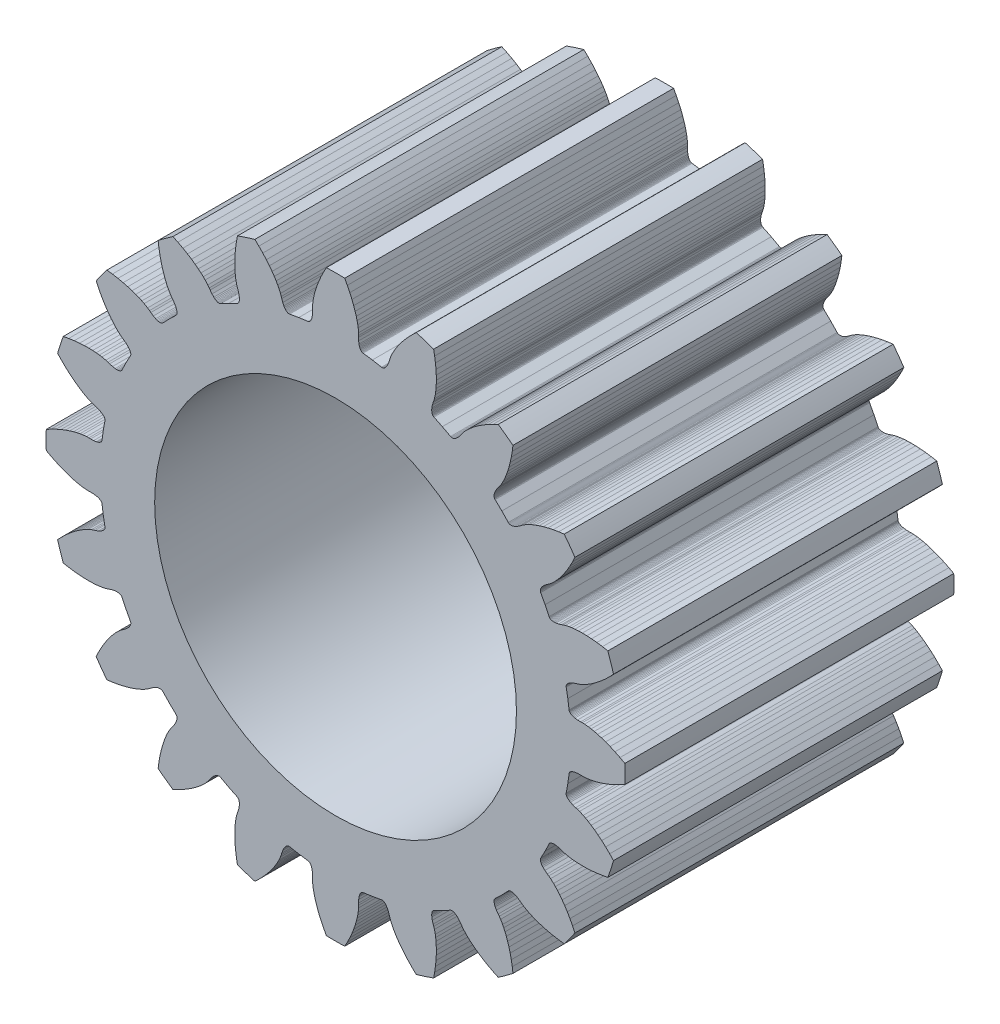
SolidWorks part; units mm, degrees
ref_plane "Front Plane" through (0, 0, 0) normal (0, 0, 1) x (1, 0, 0)
ref_plane "Top Plane" through (0, 0, 0) normal (0, 1, 0) x (1, 0, 0)
ref_plane "Right Plane" through (0, 0, 0) normal (1, 0, 0) x (0, 0, -1)
sketch "Model" plane through (0, 0, 0) normal (0, 0, 1) x (1, 0, 0)
  line L0 (8.3352, 2.3319) -> (8.2121, 2.2124)
  line L1 (8.2121, 2.2124) -> (8.0919, 2.105)
  line L2 (8.0919, 2.105) -> (7.979, 2.0124)
  line L3 (7.979, 2.0124) -> (7.871, 1.9311)
  line L4 (7.871, 1.9311) -> (7.7726, 1.8633)
  line L5 (7.7726, 1.8633) -> (7.6829, 1.8069)
  line L6 (7.6829, 1.8069) -> (7.5999, 1.7594)
  line L7 (7.5999, 1.7594) -> (7.5291, 1.7228)
  line L8 (7.5291, 1.7228) -> (7.4184, 1.6736)
  line L9 (7.4184, 1.6736) -> (7.3509, 1.6501)
  line L10 (7.3509, 1.6501) -> (7.3009, 1.6361)
  line L11 (7.3009, 1.6361) -> (7.2137, 1.6055)
  line L12 (7.2137, 1.6055) -> (7.1419, 1.5711)
  line L13 (7.1419, 1.5711) -> (7.1118, 1.5528)
  line L14 (7.1118, 1.5528) -> (7.0856, 1.5341)
  line L15 (7.0856, 1.5341) -> (7.0633, 1.515)
  line L16 (7.0633, 1.515) -> (7.0449, 1.4957)
  line L17 (7.0449, 1.4957) -> (7.0305, 1.4763)
  line L18 (7.0305, 1.4763) -> (7.0199, 1.4571)
  line L19 (7.0199, 1.4571) -> (7.0132, 1.4382)
  line L20 (7.0132, 1.4382) -> (7.0103, 1.4197)
  line L21 (7.0103, 1.4197) -> (7.0121, 1.3974)
  line L22 (7.0121, 1.3974) -> (7.062, 1.1185)
  line L23 (7.062, 1.1185) -> (7.1008, 0.8378)
  line L24 (7.1008, 0.8378) -> (7.1059, 0.8161)
  line L25 (7.1059, 0.8161) -> (7.1143, 0.7994)
  line L26 (7.1143, 0.7994) -> (7.1266, 0.7834)
  line L27 (7.1266, 0.7834) -> (7.1426, 0.7685)
  line L28 (7.1426, 0.7685) -> (7.1623, 0.7545)
  line L29 (7.1623, 0.7545) -> (7.1858, 0.7419)
  line L30 (7.1858, 0.7419) -> (7.2129, 0.7306)
  line L31 (7.2129, 0.7306) -> (7.2436, 0.7208)
  line L32 (7.2436, 0.7208) -> (7.2778, 0.7127)
  line L33 (7.2778, 0.7127) -> (7.3568, 0.7022)
  line L34 (7.3568, 0.7022) -> (7.4491, 0.7001)
  line L35 (7.4491, 0.7001) -> (7.501, 0.7023)
  line L36 (7.501, 0.7023) -> (7.5725, 0.7007)
  line L37 (7.5725, 0.7007) -> (7.6929, 0.6882)
  line L38 (7.6929, 0.6882) -> (7.7716, 0.6752)
  line L39 (7.7716, 0.6752) -> (7.8652, 0.6557)
  line L40 (7.8652, 0.6557) -> (7.968, 0.6297)
  line L41 (7.968, 0.6297) -> (8.0825, 0.5957)
  line L42 (8.0825, 0.5957) -> (8.2103, 0.5518)
  line L43 (8.2103, 0.5518) -> (8.3463, 0.4986)
  line L44 (8.3463, 0.4986) -> (8.4939, 0.4336)
  line L45 (8.4939, 0.4336) -> (8.6478, 0.358)
  line L46 (8.6478, 0.358) -> (8.7956, 0.2778)
  line L47 (8.7956, -0.2778) -> (8.6478, -0.358)
  line L48 (8.6478, -0.358) -> (8.4939, -0.4336)
  line L49 (8.4939, -0.4336) -> (8.3463, -0.4986)
  line L50 (8.3463, -0.4986) -> (8.2103, -0.5518)
  line L51 (8.2103, -0.5518) -> (8.0825, -0.5957)
  line L52 (8.0825, -0.5957) -> (7.968, -0.6297)
  line L53 (7.968, -0.6297) -> (7.8652, -0.6557)
  line L54 (7.8652, -0.6557) -> (7.7716, -0.6752)
  line L55 (7.7716, -0.6752) -> (7.6929, -0.6882)
  line L56 (7.6929, -0.6882) -> (7.5725, -0.7007)
  line L57 (7.5725, -0.7007) -> (7.501, -0.7023)
  line L58 (7.501, -0.7023) -> (7.4491, -0.7001)
  line L59 (7.4491, -0.7001) -> (7.3568, -0.7022)
  line L60 (7.3568, -0.7022) -> (7.2778, -0.7127)
  line L61 (7.2778, -0.7127) -> (7.2436, -0.7208)
  line L62 (7.2436, -0.7208) -> (7.2129, -0.7306)
  line L63 (7.2129, -0.7306) -> (7.1858, -0.7419)
  line L64 (7.1858, -0.7419) -> (7.1623, -0.7545)
  line L65 (7.1623, -0.7545) -> (7.1426, -0.7685)
  line L66 (7.1426, -0.7685) -> (7.1266, -0.7834)
  line L67 (7.1266, -0.7834) -> (7.1143, -0.7994)
  line L68 (7.1143, -0.7994) -> (7.1059, -0.8161)
  line L69 (7.1059, -0.8161) -> (7.1008, -0.8378)
  line L70 (7.1008, -0.8378) -> (7.062, -1.1185)
  line L71 (7.062, -1.1185) -> (7.0121, -1.3974)
  line L72 (7.0121, -1.3974) -> (7.0103, -1.4197)
  line L73 (7.0103, -1.4197) -> (7.0132, -1.4382)
  line L74 (7.0132, -1.4382) -> (7.0199, -1.4571)
  line L75 (7.0199, -1.4571) -> (7.0305, -1.4763)
  line L76 (7.0305, -1.4763) -> (7.0449, -1.4957)
  line L77 (7.0449, -1.4957) -> (7.0633, -1.515)
  line L78 (7.0633, -1.515) -> (7.0856, -1.5341)
  line L79 (7.0856, -1.5341) -> (7.1118, -1.5528)
  line L80 (7.1118, -1.5528) -> (7.1419, -1.5711)
  line L81 (7.1419, -1.5711) -> (7.2137, -1.6055)
  line L82 (7.2137, -1.6055) -> (7.3009, -1.6361)
  line L83 (7.3009, -1.6361) -> (7.3509, -1.6501)
  line L84 (7.3509, -1.6501) -> (7.4184, -1.6736)
  line L85 (7.4184, -1.6736) -> (7.5291, -1.7228)
  line L86 (7.5291, -1.7228) -> (7.5999, -1.7594)
  line L87 (7.5999, -1.7594) -> (7.6829, -1.8069)
  line L88 (7.6829, -1.8069) -> (7.7726, -1.8633)
  line L89 (7.7726, -1.8633) -> (7.871, -1.9311)
  line L90 (7.871, -1.9311) -> (7.979, -2.0124)
  line L91 (7.979, -2.0124) -> (8.0919, -2.105)
  line L92 (8.0919, -2.105) -> (8.2121, -2.2124)
  line L93 (8.2121, -2.2124) -> (8.3352, -2.3319)
  line L94 (8.3352, -2.3319) -> (8.451, -2.4538)
  line L95 (8.2793, -2.9822) -> (8.1139, -3.0128)
  line L96 (8.1139, -3.0128) -> (7.9441, -3.0371)
  line L97 (7.9441, -3.0371) -> (7.7837, -3.0533)
  line L98 (7.7837, -3.0533) -> (7.638, -3.0619)
  line L99 (7.638, -3.0619) -> (7.5029, -3.0642)
  line L100 (7.5029, -3.0642) -> (7.3834, -3.0611)
  line L101 (7.3834, -3.0611) -> (7.2777, -3.0541)
  line L102 (7.2777, -3.0541) -> (7.1826, -3.0437)
  line L103 (7.1826, -3.0437) -> (7.1038, -3.0317)
  line L104 (7.1038, -3.0317) -> (6.9854, -3.0065)
  line L105 (6.9854, -3.0065) -> (6.9169, -2.9858)
  line L106 (6.9169, -2.9858) -> (6.8682, -2.9677)
  line L107 (6.8682, -2.9677) -> (6.7797, -2.9412)
  line L108 (6.7797, -2.9412) -> (6.7014, -2.9268)
  line L109 (6.7014, -2.9268) -> (6.6663, -2.9239)
  line L110 (6.6663, -2.9239) -> (6.6341, -2.9237)
  line L111 (6.6341, -2.9237) -> (6.6048, -2.9261)
  line L112 (6.6048, -2.9261) -> (6.5786, -2.9309)
  line L113 (6.5786, -2.9309) -> (6.5555, -2.938)
  line L114 (6.5555, -2.938) -> (6.5357, -2.9473)
  line L115 (6.5357, -2.9473) -> (6.5191, -2.9587)
  line L116 (6.5191, -2.9587) -> (6.5059, -2.972)
  line L117 (6.5059, -2.972) -> (6.4943, -2.9911)
  line L118 (6.4943, -2.9911) -> (6.3707, -3.246)
  line L119 (6.3707, -3.246) -> (6.2371, -3.4959)
  line L120 (6.2371, -3.4959) -> (6.2285, -3.5165)
  line L121 (6.2285, -3.5165) -> (6.2255, -3.535)
  line L122 (6.2255, -3.535) -> (6.226, -3.5551)
  line L123 (6.226, -3.5551) -> (6.2302, -3.5766)
  line L124 (6.2302, -3.5766) -> (6.2379, -3.5995)
  line L125 (6.2379, -3.5995) -> (6.2495, -3.6235)
  line L126 (6.2495, -3.6235) -> (6.2648, -3.6486)
  line L127 (6.2648, -3.6486) -> (6.2839, -3.6745)
  line L128 (6.2839, -3.6745) -> (6.3068, -3.7012)
  line L129 (6.3068, -3.7012) -> (6.3645, -3.7561)
  line L130 (6.3645, -3.7561) -> (6.438, -3.8121)
  line L131 (6.438, -3.8121) -> (6.4812, -3.8409)
  line L132 (6.4812, -3.8409) -> (6.5382, -3.8841)
  line L133 (6.5382, -3.8841) -> (6.6282, -3.9651)
  line L134 (6.6282, -3.9651) -> (6.6842, -4.0218)
  line L135 (6.6842, -4.0218) -> (6.7485, -4.0926)
  line L136 (6.7485, -4.0926) -> (6.8164, -4.174)
  line L137 (6.8164, -4.174) -> (6.889, -4.2689)
  line L138 (6.889, -4.2689) -> (6.9666, -4.3795)
  line L139 (6.9666, -4.3795) -> (7.0454, -4.5025)
  line L140 (7.0454, -4.5025) -> (7.1265, -4.6418)
  line L141 (7.1265, -4.6418) -> (7.2066, -4.7935)
  line L142 (7.2066, -4.7935) -> (7.2791, -4.9452)
  line L143 (6.9525, -5.3947) -> (6.7858, -5.3726)
  line L144 (6.7858, -5.3726) -> (6.6168, -5.3434)
  line L145 (6.6168, -5.3434) -> (6.4593, -5.3092)
  line L146 (6.4593, -5.3092) -> (6.318, -5.2723)
  line L147 (6.318, -5.2723) -> (6.1888, -5.2327)
  line L148 (6.1888, -5.2327) -> (6.0761, -5.1929)
  line L149 (6.0761, -5.1929) -> (5.9777, -5.1535)
  line L150 (5.9777, -5.1535) -> (5.8905, -5.1143)
  line L151 (5.8905, -5.1143) -> (5.8192, -5.0785)
  line L152 (5.8192, -5.0785) -> (5.7145, -5.0179)
  line L153 (5.7145, -5.0179) -> (5.6557, -4.9771)
  line L154 (5.6557, -4.9771) -> (5.615, -4.9448)
  line L155 (5.615, -4.9448) -> (5.539, -4.8923)
  line L156 (5.539, -4.8923) -> (5.4689, -4.8544)
  line L157 (5.4689, -4.8544) -> (5.4365, -4.8408)
  line L158 (5.4365, -4.8408) -> (5.4059, -4.8307)
  line L159 (5.4059, -4.8307) -> (5.3773, -4.8239)
  line L160 (5.3773, -4.8239) -> (5.3509, -4.8203)
  line L161 (5.3509, -4.8203) -> (5.3268, -4.82)
  line L162 (5.3268, -4.82) -> (5.305, -4.8227)
  line L163 (5.305, -4.8227) -> (5.2858, -4.8284)
  line L164 (5.2858, -4.8284) -> (5.2691, -4.837)
  line L165 (5.2691, -4.837) -> (5.2522, -4.8516)
  line L166 (5.2522, -4.8516) -> (5.0558, -5.0558)
  line L167 (5.0558, -5.0558) -> (4.8516, -5.2522)
  line L168 (4.8516, -5.2522) -> (4.837, -5.2691)
  line L169 (4.837, -5.2691) -> (4.8284, -5.2858)
  line L170 (4.8284, -5.2858) -> (4.8227, -5.305)
  line L171 (4.8227, -5.305) -> (4.82, -5.3268)
  line L172 (4.82, -5.3268) -> (4.8203, -5.3509)
  line L173 (4.8203, -5.3509) -> (4.8239, -5.3773)
  line L174 (4.8239, -5.3773) -> (4.8307, -5.4059)
  line L175 (4.8307, -5.4059) -> (4.8408, -5.4365)
  line L176 (4.8408, -5.4365) -> (4.8544, -5.4689)
  line L177 (4.8544, -5.4689) -> (4.8923, -5.539)
  line L178 (4.8923, -5.539) -> (4.9448, -5.615)
  line L179 (4.9448, -5.615) -> (4.9771, -5.6557)
  line L180 (4.9771, -5.6557) -> (5.0179, -5.7145)
  line L181 (5.0179, -5.7145) -> (5.0785, -5.8192)
  line L182 (5.0785, -5.8192) -> (5.1143, -5.8905)
  line L183 (5.1143, -5.8905) -> (5.1535, -5.9777)
  line L184 (5.1535, -5.9777) -> (5.1929, -6.0761)
  line L185 (5.1929, -6.0761) -> (5.2327, -6.1888)
  line L186 (5.2327, -6.1888) -> (5.2723, -6.318)
  line L187 (5.2723, -6.318) -> (5.3092, -6.4593)
  line L188 (5.3092, -6.4593) -> (5.3434, -6.6168)
  line L189 (5.3434, -6.6168) -> (5.3726, -6.7858)
  line L190 (5.3726, -6.7858) -> (5.3947, -6.9525)
  line L191 (4.9452, -7.2791) -> (4.7935, -7.2066)
  line L192 (4.7935, -7.2066) -> (4.6418, -7.1265)
  line L193 (4.6418, -7.1265) -> (4.5025, -7.0454)
  line L194 (4.5025, -7.0454) -> (4.3795, -6.9666)
  line L195 (4.3795, -6.9666) -> (4.2689, -6.889)
  line L196 (4.2689, -6.889) -> (4.174, -6.8164)
  line L197 (4.174, -6.8164) -> (4.0926, -6.7485)
  line L198 (4.0926, -6.7485) -> (4.0218, -6.6842)
  line L199 (4.0218, -6.6842) -> (3.9651, -6.6282)
  line L200 (3.9651, -6.6282) -> (3.8841, -6.5382)
  line L201 (3.8841, -6.5382) -> (3.8409, -6.4812)
  line L202 (3.8409, -6.4812) -> (3.8121, -6.438)
  line L203 (3.8121, -6.438) -> (3.7561, -6.3645)
  line L204 (3.7561, -6.3645) -> (3.7012, -6.3068)
  line L205 (3.7012, -6.3068) -> (3.6745, -6.2839)
  line L206 (3.6745, -6.2839) -> (3.6486, -6.2648)
  line L207 (3.6486, -6.2648) -> (3.6235, -6.2495)
  line L208 (3.6235, -6.2495) -> (3.5995, -6.2379)
  line L209 (3.5995, -6.2379) -> (3.5766, -6.2302)
  line L210 (3.5766, -6.2302) -> (3.5551, -6.226)
  line L211 (3.5551, -6.226) -> (3.535, -6.2255)
  line L212 (3.535, -6.2255) -> (3.5165, -6.2285)
  line L213 (3.5165, -6.2285) -> (3.4959, -6.2371)
  line L214 (3.4959, -6.2371) -> (3.246, -6.3707)
  line L215 (3.246, -6.3707) -> (2.9911, -6.4943)
  line L216 (2.9911, -6.4943) -> (2.972, -6.5059)
  line L217 (2.972, -6.5059) -> (2.9587, -6.5191)
  line L218 (2.9587, -6.5191) -> (2.9473, -6.5357)
  line L219 (2.9473, -6.5357) -> (2.938, -6.5555)
  line L220 (2.938, -6.5555) -> (2.9309, -6.5786)
  line L221 (2.9309, -6.5786) -> (2.9261, -6.6048)
  line L222 (2.9261, -6.6048) -> (2.9237, -6.6341)
  line L223 (2.9237, -6.6341) -> (2.9239, -6.6663)
  line L224 (2.9239, -6.6663) -> (2.9268, -6.7014)
  line L225 (2.9268, -6.7014) -> (2.9412, -6.7797)
  line L226 (2.9412, -6.7797) -> (2.9677, -6.8682)
  line L227 (2.9677, -6.8682) -> (2.9858, -6.9169)
  line L228 (2.9858, -6.9169) -> (3.0065, -6.9854)
  line L229 (3.0065, -6.9854) -> (3.0317, -7.1038)
  line L230 (3.0317, -7.1038) -> (3.0437, -7.1826)
  line L231 (3.0437, -7.1826) -> (3.0541, -7.2777)
  line L232 (3.0541, -7.2777) -> (3.0611, -7.3834)
  line L233 (3.0611, -7.3834) -> (3.0642, -7.5029)
  line L234 (3.0642, -7.5029) -> (3.0619, -7.638)
  line L235 (3.0619, -7.638) -> (3.0533, -7.7837)
  line L236 (3.0533, -7.7837) -> (3.0371, -7.9441)
  line L237 (3.0371, -7.9441) -> (3.0128, -8.1139)
  line L238 (3.0128, -8.1139) -> (2.9822, -8.2793)
  line L239 (2.4538, -8.451) -> (2.3319, -8.3352)
  line L240 (2.3319, -8.3352) -> (2.2124, -8.2121)
  line L241 (2.2124, -8.2121) -> (2.105, -8.0919)
  line L242 (2.105, -8.0919) -> (2.0124, -7.979)
  line L243 (2.0124, -7.979) -> (1.9311, -7.871)
  line L244 (1.9311, -7.871) -> (1.8633, -7.7726)
  line L245 (1.8633, -7.7726) -> (1.8069, -7.6829)
  line L246 (1.8069, -7.6829) -> (1.7594, -7.5999)
  line L247 (1.7594, -7.5999) -> (1.7228, -7.5291)
  line L248 (1.7228, -7.5291) -> (1.6736, -7.4184)
  line L249 (1.6736, -7.4184) -> (1.6501, -7.3509)
  line L250 (1.6501, -7.3509) -> (1.6361, -7.3009)
  line L251 (1.6361, -7.3009) -> (1.6055, -7.2137)
  line L252 (1.6055, -7.2137) -> (1.5711, -7.1419)
  line L253 (1.5711, -7.1419) -> (1.5528, -7.1118)
  line L254 (1.5528, -7.1118) -> (1.5341, -7.0856)
  line L255 (1.5341, -7.0856) -> (1.515, -7.0633)
  line L256 (1.515, -7.0633) -> (1.4957, -7.0449)
  line L257 (1.4957, -7.0449) -> (1.4763, -7.0305)
  line L258 (1.4763, -7.0305) -> (1.4571, -7.0199)
  line L259 (1.4571, -7.0199) -> (1.4382, -7.0132)
  line L260 (1.4382, -7.0132) -> (1.4197, -7.0103)
  line L261 (1.4197, -7.0103) -> (1.3974, -7.0121)
  line L262 (1.3974, -7.0121) -> (1.1185, -7.062)
  line L263 (1.1185, -7.062) -> (0.8378, -7.1008)
  line L264 (0.8378, -7.1008) -> (0.8161, -7.1059)
  line L265 (0.8161, -7.1059) -> (0.7994, -7.1143)
  line L266 (0.7994, -7.1143) -> (0.7834, -7.1266)
  line L267 (0.7834, -7.1266) -> (0.7685, -7.1426)
  line L268 (0.7685, -7.1426) -> (0.7545, -7.1623)
  line L269 (0.7545, -7.1623) -> (0.7419, -7.1858)
  line L270 (0.7419, -7.1858) -> (0.7306, -7.2129)
  line L271 (0.7306, -7.2129) -> (0.7208, -7.2436)
  line L272 (0.7208, -7.2436) -> (0.7127, -7.2778)
  line L273 (0.7127, -7.2778) -> (0.7022, -7.3568)
  line L274 (0.7022, -7.3568) -> (0.7001, -7.4491)
  line L275 (0.7001, -7.4491) -> (0.7023, -7.501)
  line L276 (0.7023, -7.501) -> (0.7007, -7.5725)
  line L277 (0.7007, -7.5725) -> (0.6882, -7.6929)
  line L278 (0.6882, -7.6929) -> (0.6752, -7.7716)
  line L279 (0.6752, -7.7716) -> (0.6557, -7.8652)
  line L280 (0.6557, -7.8652) -> (0.6297, -7.968)
  line L281 (0.6297, -7.968) -> (0.5957, -8.0825)
  line L282 (0.5957, -8.0825) -> (0.5518, -8.2103)
  line L283 (0.5518, -8.2103) -> (0.4986, -8.3463)
  line L284 (0.4986, -8.3463) -> (0.4336, -8.4939)
  line L285 (0.4336, -8.4939) -> (0.358, -8.6478)
  line L286 (0.358, -8.6478) -> (0.2778, -8.7956)
  line L287 (-0.2778, -8.7956) -> (-0.358, -8.6478)
  line L288 (-0.358, -8.6478) -> (-0.4336, -8.4939)
  line L289 (-0.4336, -8.4939) -> (-0.4986, -8.3463)
  line L290 (-0.4986, -8.3463) -> (-0.5518, -8.2103)
  line L291 (-0.5518, -8.2103) -> (-0.5957, -8.0825)
  line L292 (-0.5957, -8.0825) -> (-0.6297, -7.968)
  line L293 (-0.6297, -7.968) -> (-0.6557, -7.8652)
  line L294 (-0.6557, -7.8652) -> (-0.6752, -7.7716)
  line L295 (-0.6752, -7.7716) -> (-0.6882, -7.6929)
  line L296 (-0.6882, -7.6929) -> (-0.7007, -7.5725)
  line L297 (-0.7007, -7.5725) -> (-0.7023, -7.501)
  line L298 (-0.7023, -7.501) -> (-0.7001, -7.4491)
  line L299 (-0.7001, -7.4491) -> (-0.7022, -7.3568)
  line L300 (-0.7022, -7.3568) -> (-0.7127, -7.2778)
  line L301 (-0.7127, -7.2778) -> (-0.7208, -7.2436)
  line L302 (-0.7208, -7.2436) -> (-0.7306, -7.2129)
  line L303 (-0.7306, -7.2129) -> (-0.7419, -7.1858)
  line L304 (-0.7419, -7.1858) -> (-0.7545, -7.1623)
  line L305 (-0.7545, -7.1623) -> (-0.7685, -7.1426)
  line L306 (-0.7685, -7.1426) -> (-0.7834, -7.1266)
  line L307 (-0.7834, -7.1266) -> (-0.7994, -7.1143)
  line L308 (-0.7994, -7.1143) -> (-0.8161, -7.1059)
  line L309 (-0.8161, -7.1059) -> (-0.8378, -7.1008)
  line L310 (-0.8378, -7.1008) -> (-1.1185, -7.062)
  line L311 (-1.1185, -7.062) -> (-1.3974, -7.0121)
  line L312 (-1.3974, -7.0121) -> (-1.4197, -7.0103)
  line L313 (-1.4197, -7.0103) -> (-1.4382, -7.0132)
  line L314 (-1.4382, -7.0132) -> (-1.4571, -7.0199)
  line L315 (-1.4571, -7.0199) -> (-1.4763, -7.0305)
  line L316 (-1.4763, -7.0305) -> (-1.4957, -7.0449)
  line L317 (-1.4957, -7.0449) -> (-1.515, -7.0633)
  line L318 (-1.515, -7.0633) -> (-1.5341, -7.0856)
  line L319 (-1.5341, -7.0856) -> (-1.5528, -7.1118)
  line L320 (-1.5528, -7.1118) -> (-1.5711, -7.1419)
  line L321 (-1.5711, -7.1419) -> (-1.6055, -7.2137)
  line L322 (-1.6055, -7.2137) -> (-1.6361, -7.3009)
  line L323 (-1.6361, -7.3009) -> (-1.6501, -7.3509)
  line L324 (-1.6501, -7.3509) -> (-1.6736, -7.4184)
  line L325 (-1.6736, -7.4184) -> (-1.7228, -7.5291)
  line L326 (-1.7228, -7.5291) -> (-1.7594, -7.5999)
  line L327 (-1.7594, -7.5999) -> (-1.8069, -7.6829)
  line L328 (-1.8069, -7.6829) -> (-1.8633, -7.7726)
  line L329 (-1.8633, -7.7726) -> (-1.9311, -7.871)
  line L330 (-1.9311, -7.871) -> (-2.0124, -7.979)
  line L331 (-2.0124, -7.979) -> (-2.105, -8.0919)
  line L332 (-2.105, -8.0919) -> (-2.2124, -8.2121)
  line L333 (-2.2124, -8.2121) -> (-2.3319, -8.3352)
  line L334 (-2.3319, -8.3352) -> (-2.4538, -8.451)
  line L335 (-2.9822, -8.2793) -> (-3.0128, -8.1139)
  line L336 (-3.0128, -8.1139) -> (-3.0371, -7.9441)
  line L337 (-3.0371, -7.9441) -> (-3.0533, -7.7837)
  line L338 (-3.0533, -7.7837) -> (-3.0619, -7.638)
  line L339 (-3.0619, -7.638) -> (-3.0642, -7.5029)
  line L340 (-3.0642, -7.5029) -> (-3.0611, -7.3834)
  line L341 (-3.0611, -7.3834) -> (-3.0541, -7.2777)
  line L342 (-3.0541, -7.2777) -> (-3.0437, -7.1826)
  line L343 (-3.0437, -7.1826) -> (-3.0317, -7.1038)
  line L344 (-3.0317, -7.1038) -> (-3.0065, -6.9854)
  line L345 (-3.0065, -6.9854) -> (-2.9858, -6.9169)
  line L346 (-2.9858, -6.9169) -> (-2.9677, -6.8682)
  line L347 (-2.9677, -6.8682) -> (-2.9412, -6.7797)
  line L348 (-2.9412, -6.7797) -> (-2.9268, -6.7014)
  line L349 (-2.9268, -6.7014) -> (-2.9239, -6.6663)
  line L350 (-2.9239, -6.6663) -> (-2.9237, -6.6341)
  line L351 (-2.9237, -6.6341) -> (-2.9261, -6.6048)
  line L352 (-2.9261, -6.6048) -> (-2.9309, -6.5786)
  line L353 (-2.9309, -6.5786) -> (-2.938, -6.5555)
  line L354 (-2.938, -6.5555) -> (-2.9473, -6.5357)
  line L355 (-2.9473, -6.5357) -> (-2.9587, -6.5191)
  line L356 (-2.9587, -6.5191) -> (-2.972, -6.5059)
  line L357 (-2.972, -6.5059) -> (-2.9911, -6.4943)
  line L358 (-2.9911, -6.4943) -> (-3.246, -6.3707)
  line L359 (-3.246, -6.3707) -> (-3.4959, -6.2371)
  line L360 (-3.4959, -6.2371) -> (-3.5165, -6.2285)
  line L361 (-3.5165, -6.2285) -> (-3.535, -6.2255)
  line L362 (-3.535, -6.2255) -> (-3.5551, -6.226)
  line L363 (-3.5551, -6.226) -> (-3.5766, -6.2302)
  line L364 (-3.5766, -6.2302) -> (-3.5995, -6.2379)
  line L365 (-3.5995, -6.2379) -> (-3.6235, -6.2495)
  line L366 (-3.6235, -6.2495) -> (-3.6486, -6.2648)
  line L367 (-3.6486, -6.2648) -> (-3.6745, -6.2839)
  line L368 (-3.6745, -6.2839) -> (-3.7012, -6.3068)
  line L369 (-3.7012, -6.3068) -> (-3.7561, -6.3645)
  line L370 (-3.7561, -6.3645) -> (-3.8121, -6.438)
  line L371 (-3.8121, -6.438) -> (-3.8409, -6.4812)
  line L372 (-3.8409, -6.4812) -> (-3.8841, -6.5382)
  line L373 (-3.8841, -6.5382) -> (-3.9651, -6.6282)
  line L374 (-3.9651, -6.6282) -> (-4.0218, -6.6842)
  line L375 (-4.0218, -6.6842) -> (-4.0926, -6.7485)
  line L376 (-4.0926, -6.7485) -> (-4.174, -6.8164)
  line L377 (-4.174, -6.8164) -> (-4.2689, -6.889)
  line L378 (-4.2689, -6.889) -> (-4.3795, -6.9666)
  line L379 (-4.3795, -6.9666) -> (-4.5025, -7.0454)
  line L380 (-4.5025, -7.0454) -> (-4.6418, -7.1265)
  line L381 (-4.6418, -7.1265) -> (-4.7935, -7.2066)
  line L382 (-4.7935, -7.2066) -> (-4.9452, -7.2791)
  line L383 (-5.3947, -6.9525) -> (-5.3726, -6.7858)
  line L384 (-5.3726, -6.7858) -> (-5.3434, -6.6168)
  line L385 (-5.3434, -6.6168) -> (-5.3092, -6.4593)
  line L386 (-5.3092, -6.4593) -> (-5.2723, -6.318)
  line L387 (-5.2723, -6.318) -> (-5.2327, -6.1888)
  line L388 (-5.2327, -6.1888) -> (-5.1929, -6.0761)
  line L389 (-5.1929, -6.0761) -> (-5.1535, -5.9777)
  line L390 (-5.1535, -5.9777) -> (-5.1143, -5.8905)
  line L391 (-5.1143, -5.8905) -> (-5.0785, -5.8192)
  line L392 (-5.0785, -5.8192) -> (-5.0179, -5.7145)
  line L393 (-5.0179, -5.7145) -> (-4.9771, -5.6557)
  line L394 (-4.9771, -5.6557) -> (-4.9448, -5.615)
  line L395 (-4.9448, -5.615) -> (-4.8923, -5.539)
  line L396 (-4.8923, -5.539) -> (-4.8544, -5.4689)
  line L397 (-4.8544, -5.4689) -> (-4.8408, -5.4365)
  line L398 (-4.8408, -5.4365) -> (-4.8307, -5.4059)
  line L399 (-4.8307, -5.4059) -> (-4.8239, -5.3773)
  line L400 (-4.8239, -5.3773) -> (-4.8203, -5.3509)
  line L401 (-4.8203, -5.3509) -> (-4.82, -5.3268)
  line L402 (-4.82, -5.3268) -> (-4.8227, -5.305)
  line L403 (-4.8227, -5.305) -> (-4.8284, -5.2858)
  line L404 (-4.8284, -5.2858) -> (-4.837, -5.2691)
  line L405 (-4.837, -5.2691) -> (-4.8516, -5.2522)
  line L406 (-4.8516, -5.2522) -> (-5.0558, -5.0558)
  line L407 (-5.0558, -5.0558) -> (-5.2522, -4.8516)
  line L408 (-5.2522, -4.8516) -> (-5.2691, -4.837)
  line L409 (-5.2691, -4.837) -> (-5.2858, -4.8284)
  line L410 (-5.2858, -4.8284) -> (-5.305, -4.8227)
  line L411 (-5.305, -4.8227) -> (-5.3268, -4.82)
  line L412 (-5.3268, -4.82) -> (-5.3509, -4.8203)
  line L413 (-5.3509, -4.8203) -> (-5.3773, -4.8239)
  line L414 (-5.3773, -4.8239) -> (-5.4059, -4.8307)
  line L415 (-5.4059, -4.8307) -> (-5.4365, -4.8408)
  line L416 (-5.4365, -4.8408) -> (-5.4689, -4.8544)
  line L417 (-5.4689, -4.8544) -> (-5.539, -4.8923)
  line L418 (-5.539, -4.8923) -> (-5.615, -4.9448)
  line L419 (-5.615, -4.9448) -> (-5.6557, -4.9771)
  line L420 (-5.6557, -4.9771) -> (-5.7145, -5.0179)
  line L421 (-5.7145, -5.0179) -> (-5.8192, -5.0785)
  line L422 (-5.8192, -5.0785) -> (-5.8905, -5.1143)
  line L423 (-5.8905, -5.1143) -> (-5.9777, -5.1535)
  line L424 (-5.9777, -5.1535) -> (-6.0761, -5.1929)
  line L425 (-6.0761, -5.1929) -> (-6.1888, -5.2327)
  line L426 (-6.1888, -5.2327) -> (-6.318, -5.2723)
  line L427 (-6.318, -5.2723) -> (-6.4593, -5.3092)
  line L428 (-6.4593, -5.3092) -> (-6.6168, -5.3434)
  line L429 (-6.6168, -5.3434) -> (-6.7858, -5.3726)
  line L430 (-6.7858, -5.3726) -> (-6.9525, -5.3947)
  line L431 (-7.2791, -4.9452) -> (-7.2066, -4.7935)
  line L432 (-7.2066, -4.7935) -> (-7.1265, -4.6418)
  line L433 (-7.1265, -4.6418) -> (-7.0454, -4.5025)
  line L434 (-7.0454, -4.5025) -> (-6.9666, -4.3795)
  line L435 (-6.9666, -4.3795) -> (-6.889, -4.2689)
  line L436 (-6.889, -4.2689) -> (-6.8164, -4.174)
  line L437 (-6.8164, -4.174) -> (-6.7485, -4.0926)
  line L438 (-6.7485, -4.0926) -> (-6.6842, -4.0218)
  line L439 (-6.6842, -4.0218) -> (-6.6282, -3.9651)
  line L440 (-6.6282, -3.9651) -> (-6.5382, -3.8841)
  line L441 (-6.5382, -3.8841) -> (-6.4812, -3.8409)
  line L442 (-6.4812, -3.8409) -> (-6.438, -3.8121)
  line L443 (-6.438, -3.8121) -> (-6.3645, -3.7561)
  line L444 (-6.3645, -3.7561) -> (-6.3068, -3.7012)
  line L445 (-6.3068, -3.7012) -> (-6.2839, -3.6745)
  line L446 (-6.2839, -3.6745) -> (-6.2648, -3.6486)
  line L447 (-6.2648, -3.6486) -> (-6.2495, -3.6235)
  line L448 (-6.2495, -3.6235) -> (-6.2379, -3.5995)
  line L449 (-6.2379, -3.5995) -> (-6.2302, -3.5766)
  line L450 (-6.2302, -3.5766) -> (-6.226, -3.5551)
  line L451 (-6.226, -3.5551) -> (-6.2255, -3.535)
  line L452 (-6.2255, -3.535) -> (-6.2285, -3.5165)
  line L453 (-6.2285, -3.5165) -> (-6.2371, -3.4959)
  line L454 (-6.2371, -3.4959) -> (-6.3707, -3.246)
  line L455 (-6.3707, -3.246) -> (-6.4943, -2.9911)
  line L456 (-6.4943, -2.9911) -> (-6.5059, -2.972)
  line L457 (-6.5059, -2.972) -> (-6.5191, -2.9587)
  line L458 (-6.5191, -2.9587) -> (-6.5357, -2.9473)
  line L459 (-6.5357, -2.9473) -> (-6.5555, -2.938)
  line L460 (-6.5555, -2.938) -> (-6.5786, -2.9309)
  line L461 (-6.5786, -2.9309) -> (-6.6048, -2.9261)
  line L462 (-6.6048, -2.9261) -> (-6.6341, -2.9237)
  line L463 (-6.6341, -2.9237) -> (-6.6663, -2.9239)
  line L464 (-6.6663, -2.9239) -> (-6.7014, -2.9268)
  line L465 (-6.7014, -2.9268) -> (-6.7797, -2.9412)
  line L466 (-6.7797, -2.9412) -> (-6.8682, -2.9677)
  line L467 (-6.8682, -2.9677) -> (-6.9169, -2.9858)
  line L468 (-6.9169, -2.9858) -> (-6.9854, -3.0065)
  line L469 (-6.9854, -3.0065) -> (-7.1038, -3.0317)
  line L470 (-7.1038, -3.0317) -> (-7.1826, -3.0437)
  line L471 (-7.1826, -3.0437) -> (-7.2777, -3.0541)
  line L472 (-7.2777, -3.0541) -> (-7.3834, -3.0611)
  line L473 (-7.3834, -3.0611) -> (-7.5029, -3.0642)
  line L474 (-7.5029, -3.0642) -> (-7.638, -3.0619)
  line L475 (-7.638, -3.0619) -> (-7.7837, -3.0533)
  line L476 (-7.7837, -3.0533) -> (-7.9441, -3.0371)
  line L477 (-7.9441, -3.0371) -> (-8.1139, -3.0128)
  line L478 (-8.1139, -3.0128) -> (-8.2793, -2.9822)
  line L479 (-8.451, -2.4538) -> (-8.3352, -2.3319)
  line L480 (-8.3352, -2.3319) -> (-8.2121, -2.2124)
  line L481 (-8.2121, -2.2124) -> (-8.0919, -2.105)
  line L482 (-8.0919, -2.105) -> (-7.979, -2.0124)
  line L483 (-7.979, -2.0124) -> (-7.871, -1.9311)
  line L484 (-7.871, -1.9311) -> (-7.7726, -1.8633)
  line L485 (-7.7726, -1.8633) -> (-7.6829, -1.8069)
  line L486 (-7.6829, -1.8069) -> (-7.5999, -1.7594)
  line L487 (-7.5999, -1.7594) -> (-7.5291, -1.7228)
  line L488 (-7.5291, -1.7228) -> (-7.4184, -1.6736)
  line L489 (-7.4184, -1.6736) -> (-7.3509, -1.6501)
  line L490 (-7.3509, -1.6501) -> (-7.3009, -1.6361)
  line L491 (-7.3009, -1.6361) -> (-7.2137, -1.6055)
  line L492 (-7.2137, -1.6055) -> (-7.1419, -1.5711)
  line L493 (-7.1419, -1.5711) -> (-7.1118, -1.5528)
  line L494 (-7.1118, -1.5528) -> (-7.0856, -1.5341)
  line L495 (-7.0856, -1.5341) -> (-7.0633, -1.515)
  line L496 (-7.0633, -1.515) -> (-7.0449, -1.4957)
  line L497 (-7.0449, -1.4957) -> (-7.0305, -1.4763)
  line L498 (-7.0305, -1.4763) -> (-7.0199, -1.4571)
  line L499 (-7.0199, -1.4571) -> (-7.0132, -1.4382)
  line L500 (-7.0132, -1.4382) -> (-7.0103, -1.4197)
  line L501 (-7.0103, -1.4197) -> (-7.0121, -1.3974)
  line L502 (-7.0121, -1.3974) -> (-7.062, -1.1185)
  line L503 (-7.062, -1.1185) -> (-7.1008, -0.8378)
  line L504 (-7.1008, -0.8378) -> (-7.1059, -0.8161)
  line L505 (-7.1059, -0.8161) -> (-7.1143, -0.7994)
  line L506 (-7.1143, -0.7994) -> (-7.1266, -0.7834)
  line L507 (-7.1266, -0.7834) -> (-7.1426, -0.7685)
  line L508 (-7.1426, -0.7685) -> (-7.1623, -0.7545)
  line L509 (-7.1623, -0.7545) -> (-7.1858, -0.7419)
  line L510 (-7.1858, -0.7419) -> (-7.2129, -0.7306)
  line L511 (-7.2129, -0.7306) -> (-7.2436, -0.7208)
  line L512 (-7.2436, -0.7208) -> (-7.2778, -0.7127)
  line L513 (-7.2778, -0.7127) -> (-7.3568, -0.7022)
  line L514 (-7.3568, -0.7022) -> (-7.4491, -0.7001)
  line L515 (-7.4491, -0.7001) -> (-7.501, -0.7023)
  line L516 (-7.501, -0.7023) -> (-7.5725, -0.7007)
  line L517 (-7.5725, -0.7007) -> (-7.6929, -0.6882)
  line L518 (-7.6929, -0.6882) -> (-7.7716, -0.6752)
  line L519 (-7.7716, -0.6752) -> (-7.8652, -0.6557)
  line L520 (-7.8652, -0.6557) -> (-7.968, -0.6297)
  line L521 (-7.968, -0.6297) -> (-8.0825, -0.5957)
  line L522 (-8.0825, -0.5957) -> (-8.2103, -0.5518)
  line L523 (-8.2103, -0.5518) -> (-8.3463, -0.4986)
  line L524 (-8.3463, -0.4986) -> (-8.4939, -0.4336)
  line L525 (-8.4939, -0.4336) -> (-8.6478, -0.358)
  line L526 (-8.6478, -0.358) -> (-8.7956, -0.2778)
  line L527 (-8.7956, 0.2778) -> (-8.6478, 0.358)
  line L528 (-8.6478, 0.358) -> (-8.4939, 0.4336)
  line L529 (-8.4939, 0.4336) -> (-8.3463, 0.4986)
  line L530 (-8.3463, 0.4986) -> (-8.2103, 0.5518)
  line L531 (-8.2103, 0.5518) -> (-8.0825, 0.5957)
  line L532 (-8.0825, 0.5957) -> (-7.968, 0.6297)
  line L533 (-7.968, 0.6297) -> (-7.8652, 0.6557)
  line L534 (-7.8652, 0.6557) -> (-7.7716, 0.6752)
  line L535 (-7.7716, 0.6752) -> (-7.6929, 0.6882)
  line L536 (-7.6929, 0.6882) -> (-7.5725, 0.7007)
  line L537 (-7.5725, 0.7007) -> (-7.501, 0.7023)
  line L538 (-7.501, 0.7023) -> (-7.4491, 0.7001)
  line L539 (-7.4491, 0.7001) -> (-7.3568, 0.7022)
  line L540 (-7.3568, 0.7022) -> (-7.2778, 0.7127)
  line L541 (-7.2778, 0.7127) -> (-7.2436, 0.7208)
  line L542 (-7.2436, 0.7208) -> (-7.2129, 0.7306)
  line L543 (-7.2129, 0.7306) -> (-7.1858, 0.7419)
  line L544 (-7.1858, 0.7419) -> (-7.1623, 0.7545)
  line L545 (-7.1623, 0.7545) -> (-7.1426, 0.7685)
  line L546 (-7.1426, 0.7685) -> (-7.1266, 0.7834)
  line L547 (-7.1266, 0.7834) -> (-7.1143, 0.7994)
  line L548 (-7.1143, 0.7994) -> (-7.1059, 0.8161)
  line L549 (-7.1059, 0.8161) -> (-7.1008, 0.8378)
  line L550 (-7.1008, 0.8378) -> (-7.062, 1.1185)
  line L551 (-7.062, 1.1185) -> (-7.0121, 1.3974)
  line L552 (-7.0121, 1.3974) -> (-7.0103, 1.4197)
  line L553 (-7.0103, 1.4197) -> (-7.0132, 1.4382)
  line L554 (-7.0132, 1.4382) -> (-7.0199, 1.4571)
  line L555 (-7.0199, 1.4571) -> (-7.0305, 1.4763)
  line L556 (-7.0305, 1.4763) -> (-7.0449, 1.4957)
  line L557 (-7.0449, 1.4957) -> (-7.0633, 1.515)
  line L558 (-7.0633, 1.515) -> (-7.0856, 1.5341)
  line L559 (-7.0856, 1.5341) -> (-7.1118, 1.5528)
  line L560 (-7.1118, 1.5528) -> (-7.1419, 1.5711)
  line L561 (-7.1419, 1.5711) -> (-7.2137, 1.6055)
  line L562 (-7.2137, 1.6055) -> (-7.3009, 1.6361)
  line L563 (-7.3009, 1.6361) -> (-7.3509, 1.6501)
  line L564 (-7.3509, 1.6501) -> (-7.4184, 1.6736)
  line L565 (-7.4184, 1.6736) -> (-7.5291, 1.7228)
  line L566 (-7.5291, 1.7228) -> (-7.5999, 1.7594)
  line L567 (-7.5999, 1.7594) -> (-7.6829, 1.8069)
  line L568 (-7.6829, 1.8069) -> (-7.7726, 1.8633)
  line L569 (-7.7726, 1.8633) -> (-7.871, 1.9311)
  line L570 (-7.871, 1.9311) -> (-7.979, 2.0124)
  line L571 (-7.979, 2.0124) -> (-8.0919, 2.105)
  line L572 (-8.0919, 2.105) -> (-8.2121, 2.2124)
  line L573 (-8.2121, 2.2124) -> (-8.3352, 2.3319)
  line L574 (-8.3352, 2.3319) -> (-8.451, 2.4538)
  line L575 (-8.2793, 2.9822) -> (-8.1139, 3.0128)
  line L576 (-8.1139, 3.0128) -> (-7.9441, 3.0371)
  line L577 (-7.9441, 3.0371) -> (-7.7837, 3.0533)
  line L578 (-7.7837, 3.0533) -> (-7.638, 3.0619)
  line L579 (-7.638, 3.0619) -> (-7.5029, 3.0642)
  line L580 (-7.5029, 3.0642) -> (-7.3834, 3.0611)
  line L581 (-7.3834, 3.0611) -> (-7.2777, 3.0541)
  line L582 (-7.2777, 3.0541) -> (-7.1826, 3.0437)
  line L583 (-7.1826, 3.0437) -> (-7.1038, 3.0317)
  line L584 (-7.1038, 3.0317) -> (-6.9854, 3.0065)
  line L585 (-6.9854, 3.0065) -> (-6.9169, 2.9858)
  line L586 (-6.9169, 2.9858) -> (-6.8682, 2.9677)
  line L587 (-6.8682, 2.9677) -> (-6.7797, 2.9412)
  line L588 (-6.7797, 2.9412) -> (-6.7014, 2.9268)
  line L589 (-6.7014, 2.9268) -> (-6.6663, 2.9239)
  line L590 (-6.6663, 2.9239) -> (-6.6341, 2.9237)
  line L591 (-6.6341, 2.9237) -> (-6.6048, 2.9261)
  line L592 (-6.6048, 2.9261) -> (-6.5786, 2.9309)
  line L593 (-6.5786, 2.9309) -> (-6.5555, 2.938)
  line L594 (-6.5555, 2.938) -> (-6.5357, 2.9473)
  line L595 (-6.5357, 2.9473) -> (-6.5191, 2.9587)
  line L596 (-6.5191, 2.9587) -> (-6.5059, 2.972)
  line L597 (-6.5059, 2.972) -> (-6.4943, 2.9911)
  line L598 (-6.4943, 2.9911) -> (-6.3707, 3.246)
  line L599 (-6.3707, 3.246) -> (-6.2371, 3.4959)
  line L600 (-6.2371, 3.4959) -> (-6.2285, 3.5165)
  line L601 (-6.2285, 3.5165) -> (-6.2255, 3.535)
  line L602 (-6.2255, 3.535) -> (-6.226, 3.5551)
  line L603 (-6.226, 3.5551) -> (-6.2302, 3.5766)
  line L604 (-6.2302, 3.5766) -> (-6.2379, 3.5995)
  line L605 (-6.2379, 3.5995) -> (-6.2495, 3.6235)
  line L606 (-6.2495, 3.6235) -> (-6.2648, 3.6486)
  line L607 (-6.2648, 3.6486) -> (-6.2839, 3.6745)
  line L608 (-6.2839, 3.6745) -> (-6.3068, 3.7012)
  line L609 (-6.3068, 3.7012) -> (-6.3645, 3.7561)
  line L610 (-6.3645, 3.7561) -> (-6.438, 3.8121)
  line L611 (-6.438, 3.8121) -> (-6.4812, 3.8409)
  line L612 (-6.4812, 3.8409) -> (-6.5382, 3.8841)
  line L613 (-6.5382, 3.8841) -> (-6.6282, 3.9651)
  line L614 (-6.6282, 3.9651) -> (-6.6842, 4.0218)
  line L615 (-6.6842, 4.0218) -> (-6.7485, 4.0926)
  line L616 (-6.7485, 4.0926) -> (-6.8164, 4.174)
  line L617 (-6.8164, 4.174) -> (-6.889, 4.2689)
  line L618 (-6.889, 4.2689) -> (-6.9666, 4.3795)
  line L619 (-6.9666, 4.3795) -> (-7.0454, 4.5025)
  line L620 (-7.0454, 4.5025) -> (-7.1265, 4.6418)
  line L621 (-7.1265, 4.6418) -> (-7.2066, 4.7935)
  line L622 (-7.2066, 4.7935) -> (-7.2791, 4.9452)
  line L623 (-6.9525, 5.3947) -> (-6.7858, 5.3726)
  line L624 (-6.7858, 5.3726) -> (-6.6168, 5.3434)
  line L625 (-6.6168, 5.3434) -> (-6.4593, 5.3092)
  line L626 (-6.4593, 5.3092) -> (-6.318, 5.2723)
  line L627 (-6.318, 5.2723) -> (-6.1888, 5.2327)
  line L628 (-6.1888, 5.2327) -> (-6.0761, 5.1929)
  line L629 (-6.0761, 5.1929) -> (-5.9777, 5.1535)
  line L630 (-5.9777, 5.1535) -> (-5.8905, 5.1143)
  line L631 (-5.8905, 5.1143) -> (-5.8192, 5.0785)
  line L632 (-5.8192, 5.0785) -> (-5.7145, 5.0179)
  line L633 (-5.7145, 5.0179) -> (-5.6557, 4.9771)
  line L634 (-5.6557, 4.9771) -> (-5.615, 4.9448)
  line L635 (-5.615, 4.9448) -> (-5.539, 4.8923)
  line L636 (-5.539, 4.8923) -> (-5.4689, 4.8544)
  line L637 (-5.4689, 4.8544) -> (-5.4365, 4.8408)
  line L638 (-5.4365, 4.8408) -> (-5.4059, 4.8307)
  line L639 (-5.4059, 4.8307) -> (-5.3773, 4.8239)
  line L640 (-5.3773, 4.8239) -> (-5.3509, 4.8203)
  line L641 (-5.3509, 4.8203) -> (-5.3268, 4.82)
  line L642 (-5.3268, 4.82) -> (-5.305, 4.8227)
  line L643 (-5.305, 4.8227) -> (-5.2858, 4.8284)
  line L644 (-5.2858, 4.8284) -> (-5.2691, 4.837)
  line L645 (-5.2691, 4.837) -> (-5.2522, 4.8516)
  line L646 (-5.2522, 4.8516) -> (-5.0558, 5.0558)
  line L647 (-5.0558, 5.0558) -> (-4.8516, 5.2522)
  line L648 (-4.8516, 5.2522) -> (-4.837, 5.2691)
  line L649 (-4.837, 5.2691) -> (-4.8284, 5.2858)
  line L650 (-4.8284, 5.2858) -> (-4.8227, 5.305)
  line L651 (-4.8227, 5.305) -> (-4.82, 5.3268)
  line L652 (-4.82, 5.3268) -> (-4.8203, 5.3509)
  line L653 (-4.8203, 5.3509) -> (-4.8239, 5.3773)
  line L654 (-4.8239, 5.3773) -> (-4.8307, 5.4059)
  line L655 (-4.8307, 5.4059) -> (-4.8408, 5.4365)
  line L656 (-4.8408, 5.4365) -> (-4.8544, 5.4689)
  line L657 (-4.8544, 5.4689) -> (-4.8923, 5.539)
  line L658 (-4.8923, 5.539) -> (-4.9448, 5.615)
  line L659 (-4.9448, 5.615) -> (-4.9771, 5.6557)
  line L660 (-4.9771, 5.6557) -> (-5.0179, 5.7145)
  line L661 (-5.0179, 5.7145) -> (-5.0785, 5.8192)
  line L662 (-5.0785, 5.8192) -> (-5.1143, 5.8905)
  line L663 (-5.1143, 5.8905) -> (-5.1535, 5.9777)
  line L664 (-5.1535, 5.9777) -> (-5.1929, 6.0761)
  line L665 (-5.1929, 6.0761) -> (-5.2327, 6.1888)
  line L666 (-5.2327, 6.1888) -> (-5.2723, 6.318)
  line L667 (-5.2723, 6.318) -> (-5.3092, 6.4593)
  line L668 (-5.3092, 6.4593) -> (-5.3434, 6.6168)
  line L669 (-5.3434, 6.6168) -> (-5.3726, 6.7858)
  line L670 (-5.3726, 6.7858) -> (-5.3947, 6.9525)
  line L671 (-4.9452, 7.2791) -> (-4.7935, 7.2066)
  line L672 (-4.7935, 7.2066) -> (-4.6418, 7.1265)
  line L673 (-4.6418, 7.1265) -> (-4.5025, 7.0454)
  line L674 (-4.5025, 7.0454) -> (-4.3795, 6.9666)
  line L675 (-4.3795, 6.9666) -> (-4.2689, 6.889)
  line L676 (-4.2689, 6.889) -> (-4.174, 6.8164)
  line L677 (-4.174, 6.8164) -> (-4.0926, 6.7485)
  line L678 (-4.0926, 6.7485) -> (-4.0218, 6.6842)
  line L679 (-4.0218, 6.6842) -> (-3.9651, 6.6282)
  line L680 (-3.9651, 6.6282) -> (-3.8841, 6.5382)
  line L681 (-3.8841, 6.5382) -> (-3.8409, 6.4812)
  line L682 (-3.8409, 6.4812) -> (-3.8121, 6.438)
  line L683 (-3.8121, 6.438) -> (-3.7561, 6.3645)
  line L684 (-3.7561, 6.3645) -> (-3.7012, 6.3068)
  line L685 (-3.7012, 6.3068) -> (-3.6745, 6.2839)
  line L686 (-3.6745, 6.2839) -> (-3.6486, 6.2648)
  line L687 (-3.6486, 6.2648) -> (-3.6235, 6.2495)
  line L688 (-3.6235, 6.2495) -> (-3.5995, 6.2379)
  line L689 (-3.5995, 6.2379) -> (-3.5766, 6.2302)
  line L690 (-3.5766, 6.2302) -> (-3.5551, 6.226)
  line L691 (-3.5551, 6.226) -> (-3.535, 6.2255)
  line L692 (-3.535, 6.2255) -> (-3.5165, 6.2285)
  line L693 (-3.5165, 6.2285) -> (-3.4959, 6.2371)
  line L694 (-3.4959, 6.2371) -> (-3.246, 6.3707)
  line L695 (-3.246, 6.3707) -> (-2.9911, 6.4943)
  line L696 (-2.9911, 6.4943) -> (-2.972, 6.5059)
  line L697 (-2.972, 6.5059) -> (-2.9587, 6.5191)
  line L698 (-2.9587, 6.5191) -> (-2.9473, 6.5357)
  line L699 (-2.9473, 6.5357) -> (-2.938, 6.5555)
  line L700 (-2.938, 6.5555) -> (-2.9309, 6.5786)
  line L701 (-2.9309, 6.5786) -> (-2.9261, 6.6048)
  line L702 (-2.9261, 6.6048) -> (-2.9237, 6.6341)
  line L703 (-2.9237, 6.6341) -> (-2.9239, 6.6663)
  line L704 (-2.9239, 6.6663) -> (-2.9268, 6.7014)
  line L705 (-2.9268, 6.7014) -> (-2.9412, 6.7797)
  line L706 (-2.9412, 6.7797) -> (-2.9677, 6.8682)
  line L707 (-2.9677, 6.8682) -> (-2.9858, 6.9169)
  line L708 (-2.9858, 6.9169) -> (-3.0065, 6.9854)
  line L709 (-3.0065, 6.9854) -> (-3.0317, 7.1038)
  line L710 (-3.0317, 7.1038) -> (-3.0437, 7.1826)
  line L711 (-3.0437, 7.1826) -> (-3.0541, 7.2777)
  line L712 (-3.0541, 7.2777) -> (-3.0611, 7.3834)
  line L713 (-3.0611, 7.3834) -> (-3.0642, 7.5029)
  line L714 (-3.0642, 7.5029) -> (-3.0619, 7.638)
  line L715 (-3.0619, 7.638) -> (-3.0533, 7.7837)
  line L716 (-3.0533, 7.7837) -> (-3.0371, 7.9441)
  line L717 (-3.0371, 7.9441) -> (-3.0128, 8.1139)
  line L718 (-3.0128, 8.1139) -> (-2.9822, 8.2793)
  line L719 (-2.4538, 8.451) -> (-2.3319, 8.3352)
  line L720 (-2.3319, 8.3352) -> (-2.2124, 8.2121)
  line L721 (-2.2124, 8.2121) -> (-2.105, 8.0919)
  line L722 (-2.105, 8.0919) -> (-2.0124, 7.979)
  line L723 (-2.0124, 7.979) -> (-1.9311, 7.871)
  line L724 (-1.9311, 7.871) -> (-1.8633, 7.7726)
  line L725 (-1.8633, 7.7726) -> (-1.8069, 7.6829)
  line L726 (-1.8069, 7.6829) -> (-1.7594, 7.5999)
  line L727 (-1.7594, 7.5999) -> (-1.7228, 7.5291)
  line L728 (-1.7228, 7.5291) -> (-1.6736, 7.4184)
  line L729 (-1.6736, 7.4184) -> (-1.6501, 7.3509)
  line L730 (-1.6501, 7.3509) -> (-1.6361, 7.3009)
  line L731 (-1.6361, 7.3009) -> (-1.6055, 7.2137)
  line L732 (-1.6055, 7.2137) -> (-1.5711, 7.1419)
  line L733 (-1.5711, 7.1419) -> (-1.5528, 7.1118)
  line L734 (-1.5528, 7.1118) -> (-1.5341, 7.0856)
  line L735 (-1.5341, 7.0856) -> (-1.515, 7.0633)
  line L736 (-1.515, 7.0633) -> (-1.4957, 7.0449)
  line L737 (-1.4957, 7.0449) -> (-1.4763, 7.0305)
  line L738 (-1.4763, 7.0305) -> (-1.4571, 7.0199)
  line L739 (-1.4571, 7.0199) -> (-1.4382, 7.0132)
  line L740 (-1.4382, 7.0132) -> (-1.4197, 7.0103)
  line L741 (-1.4197, 7.0103) -> (-1.3974, 7.0121)
  line L742 (-1.3974, 7.0121) -> (-1.1185, 7.062)
  line L743 (-1.1185, 7.062) -> (-0.8378, 7.1008)
  line L744 (-0.8378, 7.1008) -> (-0.8161, 7.1059)
  line L745 (-0.8161, 7.1059) -> (-0.7994, 7.1143)
  line L746 (-0.7994, 7.1143) -> (-0.7834, 7.1266)
  line L747 (-0.7834, 7.1266) -> (-0.7685, 7.1426)
  line L748 (-0.7685, 7.1426) -> (-0.7545, 7.1623)
  line L749 (-0.7545, 7.1623) -> (-0.7419, 7.1858)
  line L750 (-0.7419, 7.1858) -> (-0.7306, 7.2129)
  line L751 (-0.7306, 7.2129) -> (-0.7208, 7.2436)
  line L752 (-0.7208, 7.2436) -> (-0.7127, 7.2778)
  line L753 (-0.7127, 7.2778) -> (-0.7022, 7.3568)
  line L754 (-0.7022, 7.3568) -> (-0.7001, 7.4491)
  line L755 (-0.7001, 7.4491) -> (-0.7023, 7.501)
  line L756 (-0.7023, 7.501) -> (-0.7007, 7.5725)
  line L757 (-0.7007, 7.5725) -> (-0.6882, 7.6929)
  line L758 (-0.6882, 7.6929) -> (-0.6752, 7.7716)
  line L759 (-0.6752, 7.7716) -> (-0.6557, 7.8652)
  line L760 (-0.6557, 7.8652) -> (-0.6297, 7.968)
  line L761 (-0.6297, 7.968) -> (-0.5957, 8.0825)
  line L762 (-0.5957, 8.0825) -> (-0.5518, 8.2103)
  line L763 (-0.5518, 8.2103) -> (-0.4986, 8.3463)
  line L764 (-0.4986, 8.3463) -> (-0.4336, 8.4939)
  line L765 (-0.4336, 8.4939) -> (-0.358, 8.6478)
  line L766 (-0.358, 8.6478) -> (-0.2778, 8.7956)
  line L767 (0.2778, 8.7956) -> (0.358, 8.6478)
  line L768 (0.358, 8.6478) -> (0.4336, 8.4939)
  line L769 (0.4336, 8.4939) -> (0.4986, 8.3463)
  line L770 (0.4986, 8.3463) -> (0.5518, 8.2103)
  line L771 (0.5518, 8.2103) -> (0.5957, 8.0825)
  line L772 (0.5957, 8.0825) -> (0.6297, 7.968)
  line L773 (0.6297, 7.968) -> (0.6557, 7.8652)
  line L774 (0.6557, 7.8652) -> (0.6752, 7.7716)
  line L775 (0.6752, 7.7716) -> (0.6882, 7.6929)
  line L776 (0.6882, 7.6929) -> (0.7007, 7.5725)
  line L777 (0.7007, 7.5725) -> (0.7023, 7.501)
  line L778 (0.7023, 7.501) -> (0.7001, 7.4491)
  line L779 (0.7001, 7.4491) -> (0.7022, 7.3568)
  line L780 (0.7022, 7.3568) -> (0.7127, 7.2778)
  line L781 (0.7127, 7.2778) -> (0.7208, 7.2436)
  line L782 (0.7208, 7.2436) -> (0.7306, 7.2129)
  line L783 (0.7306, 7.2129) -> (0.7419, 7.1858)
  line L784 (0.7419, 7.1858) -> (0.7545, 7.1623)
  line L785 (0.7545, 7.1623) -> (0.7685, 7.1426)
  line L786 (0.7685, 7.1426) -> (0.7834, 7.1266)
  line L787 (0.7834, 7.1266) -> (0.7994, 7.1143)
  line L788 (0.7994, 7.1143) -> (0.8161, 7.1059)
  line L789 (0.8161, 7.1059) -> (0.8378, 7.1008)
  line L790 (0.8378, 7.1008) -> (1.1185, 7.062)
  line L791 (1.1185, 7.062) -> (1.3974, 7.0121)
  line L792 (1.3974, 7.0121) -> (1.4197, 7.0103)
  line L793 (1.4197, 7.0103) -> (1.4382, 7.0132)
  line L794 (1.4382, 7.0132) -> (1.4571, 7.0199)
  line L795 (1.4571, 7.0199) -> (1.4763, 7.0305)
  line L796 (1.4763, 7.0305) -> (1.4957, 7.0449)
  line L797 (1.4957, 7.0449) -> (1.515, 7.0633)
  line L798 (1.515, 7.0633) -> (1.5341, 7.0856)
  line L799 (1.5341, 7.0856) -> (1.5528, 7.1118)
  line L800 (1.5528, 7.1118) -> (1.5711, 7.1419)
  line L801 (1.5711, 7.1419) -> (1.6055, 7.2137)
  line L802 (1.6055, 7.2137) -> (1.6361, 7.3009)
  line L803 (1.6361, 7.3009) -> (1.6501, 7.3509)
  line L804 (1.6501, 7.3509) -> (1.6736, 7.4184)
  line L805 (1.6736, 7.4184) -> (1.7228, 7.5291)
  line L806 (1.7228, 7.5291) -> (1.7594, 7.5999)
  line L807 (1.7594, 7.5999) -> (1.8069, 7.6829)
  line L808 (1.8069, 7.6829) -> (1.8633, 7.7726)
  line L809 (1.8633, 7.7726) -> (1.9311, 7.871)
  line L810 (1.9311, 7.871) -> (2.0124, 7.979)
  line L811 (2.0124, 7.979) -> (2.105, 8.0919)
  line L812 (2.105, 8.0919) -> (2.2124, 8.2121)
  line L813 (2.2124, 8.2121) -> (2.3319, 8.3352)
  line L814 (2.3319, 8.3352) -> (2.4538, 8.451)
  line L815 (2.9822, 8.2793) -> (3.0128, 8.1139)
  line L816 (3.0128, 8.1139) -> (3.0371, 7.9441)
  line L817 (3.0371, 7.9441) -> (3.0533, 7.7837)
  line L818 (3.0533, 7.7837) -> (3.0619, 7.638)
  line L819 (3.0619, 7.638) -> (3.0642, 7.5029)
  line L820 (3.0642, 7.5029) -> (3.0611, 7.3834)
  line L821 (3.0611, 7.3834) -> (3.0541, 7.2777)
  line L822 (3.0541, 7.2777) -> (3.0437, 7.1826)
  line L823 (3.0437, 7.1826) -> (3.0317, 7.1038)
  line L824 (3.0317, 7.1038) -> (3.0065, 6.9854)
  line L825 (3.0065, 6.9854) -> (2.9858, 6.9169)
  line L826 (2.9858, 6.9169) -> (2.9677, 6.8682)
  line L827 (2.9677, 6.8682) -> (2.9412, 6.7797)
  line L828 (2.9412, 6.7797) -> (2.9268, 6.7014)
  line L829 (2.9268, 6.7014) -> (2.9239, 6.6663)
  line L830 (2.9239, 6.6663) -> (2.9237, 6.6341)
  line L831 (2.9237, 6.6341) -> (2.9261, 6.6048)
  line L832 (2.9261, 6.6048) -> (2.9309, 6.5786)
  line L833 (2.9309, 6.5786) -> (2.938, 6.5555)
  line L834 (2.938, 6.5555) -> (2.9473, 6.5357)
  line L835 (2.9473, 6.5357) -> (2.9587, 6.5191)
  line L836 (2.9587, 6.5191) -> (2.972, 6.5059)
  line L837 (2.972, 6.5059) -> (2.9911, 6.4943)
  line L838 (2.9911, 6.4943) -> (3.246, 6.3707)
  line L839 (3.246, 6.3707) -> (3.4959, 6.2371)
  line L840 (3.4959, 6.2371) -> (3.5165, 6.2285)
  line L841 (3.5165, 6.2285) -> (3.535, 6.2255)
  line L842 (3.535, 6.2255) -> (3.5551, 6.226)
  line L843 (3.5551, 6.226) -> (3.5766, 6.2302)
  line L844 (3.5766, 6.2302) -> (3.5995, 6.2379)
  line L845 (3.5995, 6.2379) -> (3.6235, 6.2495)
  line L846 (3.6235, 6.2495) -> (3.6486, 6.2648)
  line L847 (3.6486, 6.2648) -> (3.6745, 6.2839)
  line L848 (3.6745, 6.2839) -> (3.7012, 6.3068)
  line L849 (3.7012, 6.3068) -> (3.7561, 6.3645)
  line L850 (3.7561, 6.3645) -> (3.8121, 6.438)
  line L851 (3.8121, 6.438) -> (3.8409, 6.4812)
  line L852 (3.8409, 6.4812) -> (3.8841, 6.5382)
  line L853 (3.8841, 6.5382) -> (3.9651, 6.6282)
  line L854 (3.9651, 6.6282) -> (4.0218, 6.6842)
  line L855 (4.0218, 6.6842) -> (4.0926, 6.7485)
  line L856 (4.0926, 6.7485) -> (4.174, 6.8164)
  line L857 (4.174, 6.8164) -> (4.2689, 6.889)
  line L858 (4.2689, 6.889) -> (4.3795, 6.9666)
  line L859 (4.3795, 6.9666) -> (4.5025, 7.0454)
  line L860 (4.5025, 7.0454) -> (4.6418, 7.1265)
  line L861 (4.6418, 7.1265) -> (4.7935, 7.2066)
  line L862 (4.7935, 7.2066) -> (4.9452, 7.2791)
  line L863 (5.3947, 6.9525) -> (5.3726, 6.7858)
  line L864 (5.3726, 6.7858) -> (5.3434, 6.6168)
  line L865 (5.3434, 6.6168) -> (5.3092, 6.4593)
  line L866 (5.3092, 6.4593) -> (5.2723, 6.318)
  line L867 (5.2723, 6.318) -> (5.2327, 6.1888)
  line L868 (5.2327, 6.1888) -> (5.1929, 6.0761)
  line L869 (5.1929, 6.0761) -> (5.1535, 5.9777)
  line L870 (5.1535, 5.9777) -> (5.1143, 5.8905)
  line L871 (5.1143, 5.8905) -> (5.0785, 5.8192)
  line L872 (5.0785, 5.8192) -> (5.0179, 5.7145)
  line L873 (5.0179, 5.7145) -> (4.9771, 5.6557)
  line L874 (4.9771, 5.6557) -> (4.9448, 5.615)
  line L875 (4.9448, 5.615) -> (4.8923, 5.539)
  line L876 (4.8923, 5.539) -> (4.8544, 5.4689)
  line L877 (4.8544, 5.4689) -> (4.8408, 5.4365)
  line L878 (4.8408, 5.4365) -> (4.8307, 5.4059)
  line L879 (4.8307, 5.4059) -> (4.8239, 5.3773)
  line L880 (4.8239, 5.3773) -> (4.8203, 5.3509)
  line L881 (4.8203, 5.3509) -> (4.82, 5.3268)
  line L882 (4.82, 5.3268) -> (4.8227, 5.305)
  line L883 (4.8227, 5.305) -> (4.8284, 5.2858)
  line L884 (4.8284, 5.2858) -> (4.837, 5.2691)
  line L885 (4.837, 5.2691) -> (4.8516, 5.2522)
  line L886 (4.8516, 5.2522) -> (5.0558, 5.0558)
  line L887 (5.0558, 5.0558) -> (5.2522, 4.8516)
  line L888 (5.2522, 4.8516) -> (5.2691, 4.837)
  line L889 (5.2691, 4.837) -> (5.2858, 4.8284)
  line L890 (5.2858, 4.8284) -> (5.305, 4.8227)
  line L891 (5.305, 4.8227) -> (5.3268, 4.82)
  line L892 (5.3268, 4.82) -> (5.3509, 4.8203)
  line L893 (5.3509, 4.8203) -> (5.3773, 4.8239)
  line L894 (5.3773, 4.8239) -> (5.4059, 4.8307)
  line L895 (5.4059, 4.8307) -> (5.4365, 4.8408)
  line L896 (5.4365, 4.8408) -> (5.4689, 4.8544)
  line L897 (5.4689, 4.8544) -> (5.539, 4.8923)
  line L898 (5.539, 4.8923) -> (5.615, 4.9448)
  line L899 (5.615, 4.9448) -> (5.6557, 4.9771)
  line L900 (5.6557, 4.9771) -> (5.7145, 5.0179)
  line L901 (5.7145, 5.0179) -> (5.8192, 5.0785)
  line L902 (5.8192, 5.0785) -> (5.8905, 5.1143)
  line L903 (5.8905, 5.1143) -> (5.9777, 5.1535)
  line L904 (5.9777, 5.1535) -> (6.0761, 5.1929)
  line L905 (6.0761, 5.1929) -> (6.1888, 5.2327)
  line L906 (6.1888, 5.2327) -> (6.318, 5.2723)
  line L907 (6.318, 5.2723) -> (6.4593, 5.3092)
  line L908 (6.4593, 5.3092) -> (6.6168, 5.3434)
  line L909 (6.6168, 5.3434) -> (6.7858, 5.3726)
  line L910 (6.7858, 5.3726) -> (6.9525, 5.3947)
  line L911 (7.2791, 4.9452) -> (7.2066, 4.7935)
  line L912 (7.2066, 4.7935) -> (7.1265, 4.6418)
  line L913 (7.1265, 4.6418) -> (7.0454, 4.5025)
  line L914 (7.0454, 4.5025) -> (6.9666, 4.3795)
  line L915 (6.9666, 4.3795) -> (6.889, 4.2689)
  line L916 (6.889, 4.2689) -> (6.8164, 4.174)
  line L917 (6.8164, 4.174) -> (6.7485, 4.0926)
  line L918 (6.7485, 4.0926) -> (6.6842, 4.0218)
  line L919 (6.6842, 4.0218) -> (6.6282, 3.9651)
  line L920 (6.6282, 3.9651) -> (6.5382, 3.8841)
  line L921 (6.5382, 3.8841) -> (6.4812, 3.8409)
  line L922 (6.4812, 3.8409) -> (6.438, 3.8121)
  line L923 (6.438, 3.8121) -> (6.3645, 3.7561)
  line L924 (6.3645, 3.7561) -> (6.3068, 3.7012)
  line L925 (6.3068, 3.7012) -> (6.2839, 3.6745)
  line L926 (6.2839, 3.6745) -> (6.2648, 3.6486)
  line L927 (6.2648, 3.6486) -> (6.2495, 3.6235)
  line L928 (6.2495, 3.6235) -> (6.2379, 3.5995)
  line L929 (6.2379, 3.5995) -> (6.2302, 3.5766)
  line L930 (6.2302, 3.5766) -> (6.226, 3.5551)
  line L931 (6.226, 3.5551) -> (6.2255, 3.535)
  line L932 (6.2255, 3.535) -> (6.2285, 3.5165)
  line L933 (6.2285, 3.5165) -> (6.2371, 3.4959)
  line L934 (6.2371, 3.4959) -> (6.3707, 3.246)
  line L935 (6.3707, 3.246) -> (6.4943, 2.9911)
  line L936 (6.4943, 2.9911) -> (6.5059, 2.972)
  line L937 (6.5059, 2.972) -> (6.5191, 2.9587)
  line L938 (6.5191, 2.9587) -> (6.5357, 2.9473)
  line L939 (6.5357, 2.9473) -> (6.5555, 2.938)
  line L940 (6.5555, 2.938) -> (6.5786, 2.9309)
  line L941 (6.5786, 2.9309) -> (6.6048, 2.9261)
  line L942 (6.6048, 2.9261) -> (6.6341, 2.9237)
  line L943 (6.6341, 2.9237) -> (6.6663, 2.9239)
  line L944 (6.6663, 2.9239) -> (6.7014, 2.9268)
  line L945 (6.7014, 2.9268) -> (6.7797, 2.9412)
  line L946 (6.7797, 2.9412) -> (6.8682, 2.9677)
  line L947 (6.8682, 2.9677) -> (6.9169, 2.9858)
  line L948 (6.9169, 2.9858) -> (6.9854, 3.0065)
  line L949 (6.9854, 3.0065) -> (7.1038, 3.0317)
  line L950 (7.1038, 3.0317) -> (7.1826, 3.0437)
  line L951 (7.1826, 3.0437) -> (7.2777, 3.0541)
  line L952 (7.2777, 3.0541) -> (7.3834, 3.0611)
  line L953 (7.3834, 3.0611) -> (7.5029, 3.0642)
  line L954 (7.5029, 3.0642) -> (7.638, 3.0619)
  line L955 (7.638, 3.0619) -> (7.7837, 3.0533)
  line L956 (7.7837, 3.0533) -> (7.9441, 3.0371)
  line L957 (7.9441, 3.0371) -> (8.1139, 3.0128)
  line L958 (8.1139, 3.0128) -> (8.2793, 2.9822)
  line L959 (8.451, 2.4538) -> (8.3352, 2.3319)
  line L960 (8.3352, 2.3319) -> (8.2121, 2.2124)
  line L961 (8.2121, 2.2124) -> (8.0919, 2.105)
  line L962 (8.0919, 2.105) -> (7.979, 2.0124)
  line L963 (7.979, 2.0124) -> (7.871, 1.9311)
  line L964 (7.871, 1.9311) -> (7.7726, 1.8633)
  line L965 (7.7726, 1.8633) -> (7.6829, 1.8069)
  line L966 (7.6829, 1.8069) -> (7.5999, 1.7594)
  line L967 (7.5999, 1.7594) -> (7.5291, 1.7228)
  line L968 (7.5291, 1.7228) -> (7.4184, 1.6736)
  line L969 (7.4184, 1.6736) -> (7.3509, 1.6501)
  line L970 (7.3509, 1.6501) -> (7.3009, 1.6361)
  line L971 (7.3009, 1.6361) -> (7.2137, 1.6055)
  line L972 (7.2137, 1.6055) -> (7.1419, 1.5711)
  line L973 (7.1419, 1.5711) -> (7.1118, 1.5528)
  line L974 (7.1118, 1.5528) -> (7.0856, 1.5341)
  line L975 (7.0856, 1.5341) -> (7.0633, 1.515)
  line L976 (7.0633, 1.515) -> (7.0449, 1.4957)
  line L977 (7.0449, 1.4957) -> (7.0305, 1.4763)
  line L978 (7.0305, 1.4763) -> (7.0199, 1.4571)
  line L979 (7.0199, 1.4571) -> (7.0132, 1.4382)
  line L980 (7.0132, 1.4382) -> (7.0103, 1.4197)
  line L981 (7.0103, 1.4197) -> (7.0121, 1.3974)
  line L982 (7.0121, 1.3974) -> (7.062, 1.1185)
  line L983 (7.062, 1.1185) -> (7.1008, 0.8378)
  line L984 (7.1008, 0.8378) -> (7.1059, 0.8161)
  line L985 (7.1059, 0.8161) -> (7.1143, 0.7994)
  line L986 (7.1143, 0.7994) -> (7.1266, 0.7834)
  line L987 (7.1266, 0.7834) -> (7.1426, 0.7685)
  line L988 (7.1426, 0.7685) -> (7.1623, 0.7545)
  line L989 (7.1623, 0.7545) -> (7.1858, 0.7419)
  line L990 (7.1858, 0.7419) -> (7.2129, 0.7306)
  line L991 (7.2129, 0.7306) -> (7.2436, 0.7208)
  line L992 (7.2436, 0.7208) -> (7.2778, 0.7127)
  line L993 (7.2778, 0.7127) -> (7.3568, 0.7022)
  line L994 (7.3568, 0.7022) -> (7.4491, 0.7001)
  line L995 (7.4491, 0.7001) -> (7.501, 0.7023)
  line L996 (7.501, 0.7023) -> (7.5725, 0.7007)
  line L997 (7.5725, 0.7007) -> (7.6929, 0.6882)
  line L998 (7.6929, 0.6882) -> (7.7716, 0.6752)
  line L999 (7.7716, 0.6752) -> (7.8652, 0.6557)
  line L1000 (7.8652, 0.6557) -> (7.968, 0.6297)
  line L1001 (7.968, 0.6297) -> (8.0825, 0.5957)
  line L1002 (8.0825, 0.5957) -> (8.2103, 0.5518)
  line L1003 (8.2103, 0.5518) -> (8.3463, 0.4986)
  line L1004 (8.3463, 0.4986) -> (8.4939, 0.4336)
  line L1005 (8.4939, 0.4336) -> (8.6478, 0.358)
  line L1006 (8.6478, 0.358) -> (8.7956, 0.2778)
  line L1007 (8.7956, -0.2778) -> (8.6478, -0.358)
  line L1008 (8.6478, -0.358) -> (8.4939, -0.4336)
  line L1009 (8.4939, -0.4336) -> (8.3463, -0.4986)
  line L1010 (8.3463, -0.4986) -> (8.2103, -0.5518)
  line L1011 (8.2103, -0.5518) -> (8.0825, -0.5957)
  line L1012 (8.0825, -0.5957) -> (7.968, -0.6297)
  line L1013 (7.968, -0.6297) -> (7.8652, -0.6557)
  line L1014 (7.8652, -0.6557) -> (7.7716, -0.6752)
  line L1015 (7.7716, -0.6752) -> (7.6929, -0.6882)
  line L1016 (7.6929, -0.6882) -> (7.5725, -0.7007)
  line L1017 (7.5725, -0.7007) -> (7.501, -0.7023)
  line L1018 (7.501, -0.7023) -> (7.4491, -0.7001)
  line L1019 (7.4491, -0.7001) -> (7.3568, -0.7022)
  line L1020 (7.3568, -0.7022) -> (7.2778, -0.7127)
  line L1021 (7.2778, -0.7127) -> (7.2436, -0.7208)
  line L1022 (7.2436, -0.7208) -> (7.2129, -0.7306)
  line L1023 (7.2129, -0.7306) -> (7.1858, -0.7419)
  line L1024 (7.1858, -0.7419) -> (7.1623, -0.7545)
  line L1025 (7.1623, -0.7545) -> (7.1426, -0.7685)
  line L1026 (7.1426, -0.7685) -> (7.1266, -0.7834)
  line L1027 (7.1266, -0.7834) -> (7.1143, -0.7994)
  line L1028 (7.1143, -0.7994) -> (7.1059, -0.8161)
  line L1029 (7.1059, -0.8161) -> (7.1008, -0.8378)
  line L1030 (7.1008, -0.8378) -> (7.062, -1.1185)
  line L1031 (7.062, -1.1185) -> (7.0121, -1.3974)
  line L1032 (7.0121, -1.3974) -> (7.0103, -1.4197)
  line L1033 (7.0103, -1.4197) -> (7.0132, -1.4382)
  line L1034 (7.0132, -1.4382) -> (7.0199, -1.4571)
  line L1035 (7.0199, -1.4571) -> (7.0305, -1.4763)
  line L1036 (7.0305, -1.4763) -> (7.0449, -1.4957)
  line L1037 (7.0449, -1.4957) -> (7.0633, -1.515)
  line L1038 (7.0633, -1.515) -> (7.0856, -1.5341)
  line L1039 (7.0856, -1.5341) -> (7.1118, -1.5528)
  line L1040 (7.1118, -1.5528) -> (7.1419, -1.5711)
  line L1041 (7.1419, -1.5711) -> (7.2137, -1.6055)
  line L1042 (7.2137, -1.6055) -> (7.3009, -1.6361)
  line L1043 (7.3009, -1.6361) -> (7.3509, -1.6501)
  line L1044 (7.3509, -1.6501) -> (7.4184, -1.6736)
  line L1045 (7.4184, -1.6736) -> (7.5291, -1.7228)
  line L1046 (7.5291, -1.7228) -> (7.5999, -1.7594)
  line L1047 (7.5999, -1.7594) -> (7.6829, -1.8069)
  line L1048 (7.6829, -1.8069) -> (7.7726, -1.8633)
  line L1049 (7.7726, -1.8633) -> (7.871, -1.9311)
  line L1050 (7.871, -1.9311) -> (7.979, -2.0124)
  line L1051 (7.979, -2.0124) -> (8.0919, -2.105)
  line L1052 (8.0919, -2.105) -> (8.2121, -2.2124)
  line L1053 (8.2121, -2.2124) -> (8.3352, -2.3319)
  line L1054 (8.3352, -2.3319) -> (8.451, -2.4538)
  line L1055 (8.2793, -2.9822) -> (8.1139, -3.0128)
  line L1056 (8.1139, -3.0128) -> (7.9441, -3.0371)
  line L1057 (7.9441, -3.0371) -> (7.7837, -3.0533)
  line L1058 (7.7837, -3.0533) -> (7.638, -3.0619)
  line L1059 (7.638, -3.0619) -> (7.5029, -3.0642)
  line L1060 (7.5029, -3.0642) -> (7.3834, -3.0611)
  line L1061 (7.3834, -3.0611) -> (7.2777, -3.0541)
  line L1062 (7.2777, -3.0541) -> (7.1826, -3.0437)
  line L1063 (7.1826, -3.0437) -> (7.1038, -3.0317)
  line L1064 (7.1038, -3.0317) -> (6.9854, -3.0065)
  line L1065 (6.9854, -3.0065) -> (6.9169, -2.9858)
  line L1066 (6.9169, -2.9858) -> (6.8682, -2.9677)
  line L1067 (6.8682, -2.9677) -> (6.7797, -2.9412)
  line L1068 (6.7797, -2.9412) -> (6.7014, -2.9268)
  line L1069 (6.7014, -2.9268) -> (6.6663, -2.9239)
  line L1070 (6.6663, -2.9239) -> (6.6341, -2.9237)
  line L1071 (6.6341, -2.9237) -> (6.6048, -2.9261)
  line L1072 (6.6048, -2.9261) -> (6.5786, -2.9309)
  line L1073 (6.5786, -2.9309) -> (6.5555, -2.938)
  line L1074 (6.5555, -2.938) -> (6.5357, -2.9473)
  line L1075 (6.5357, -2.9473) -> (6.5191, -2.9587)
  line L1076 (6.5191, -2.9587) -> (6.5059, -2.972)
  line L1077 (6.5059, -2.972) -> (6.4943, -2.9911)
  line L1078 (6.4943, -2.9911) -> (6.3707, -3.246)
  line L1079 (6.3707, -3.246) -> (6.2371, -3.4959)
  line L1080 (6.2371, -3.4959) -> (6.2285, -3.5165)
  line L1081 (6.2285, -3.5165) -> (6.2255, -3.535)
  line L1082 (6.2255, -3.535) -> (6.226, -3.5551)
  line L1083 (6.226, -3.5551) -> (6.2302, -3.5766)
  line L1084 (6.2302, -3.5766) -> (6.2379, -3.5995)
  line L1085 (6.2379, -3.5995) -> (6.2495, -3.6235)
  line L1086 (6.2495, -3.6235) -> (6.2648, -3.6486)
  line L1087 (6.2648, -3.6486) -> (6.2839, -3.6745)
  line L1088 (6.2839, -3.6745) -> (6.3068, -3.7012)
  line L1089 (6.3068, -3.7012) -> (6.3645, -3.7561)
  line L1090 (6.3645, -3.7561) -> (6.438, -3.8121)
  line L1091 (6.438, -3.8121) -> (6.4812, -3.8409)
  line L1092 (6.4812, -3.8409) -> (6.5382, -3.8841)
  line L1093 (6.5382, -3.8841) -> (6.6282, -3.9651)
  line L1094 (6.6282, -3.9651) -> (6.6842, -4.0218)
  line L1095 (6.6842, -4.0218) -> (6.7485, -4.0926)
  line L1096 (6.7485, -4.0926) -> (6.8164, -4.174)
  line L1097 (6.8164, -4.174) -> (6.889, -4.2689)
  line L1098 (6.889, -4.2689) -> (6.9666, -4.3795)
  line L1099 (6.9666, -4.3795) -> (7.0454, -4.5025)
  line L1100 (7.0454, -4.5025) -> (7.1265, -4.6418)
  line L1101 (7.1265, -4.6418) -> (7.2066, -4.7935)
  line L1102 (7.2066, -4.7935) -> (7.2791, -4.9452)
  line L1103 (6.9525, -5.3947) -> (6.7858, -5.3726)
  line L1104 (6.7858, -5.3726) -> (6.6168, -5.3434)
  line L1105 (6.6168, -5.3434) -> (6.4593, -5.3092)
  line L1106 (6.4593, -5.3092) -> (6.318, -5.2723)
  line L1107 (6.318, -5.2723) -> (6.1888, -5.2327)
  line L1108 (6.1888, -5.2327) -> (6.0761, -5.1929)
  line L1109 (6.0761, -5.1929) -> (5.9777, -5.1535)
  line L1110 (5.9777, -5.1535) -> (5.8905, -5.1143)
  line L1111 (5.8905, -5.1143) -> (5.8192, -5.0785)
  line L1112 (5.8192, -5.0785) -> (5.7145, -5.0179)
  line L1113 (5.7145, -5.0179) -> (5.6557, -4.9771)
  line L1114 (5.6557, -4.9771) -> (5.615, -4.9448)
  line L1115 (5.615, -4.9448) -> (5.539, -4.8923)
  line L1116 (5.539, -4.8923) -> (5.4689, -4.8544)
  line L1117 (5.4689, -4.8544) -> (5.4365, -4.8408)
  line L1118 (5.4365, -4.8408) -> (5.4059, -4.8307)
  line L1119 (5.4059, -4.8307) -> (5.3773, -4.8239)
  line L1120 (5.3773, -4.8239) -> (5.3509, -4.8203)
  line L1121 (5.3509, -4.8203) -> (5.3268, -4.82)
  line L1122 (5.3268, -4.82) -> (5.305, -4.8227)
  line L1123 (5.305, -4.8227) -> (5.2858, -4.8284)
  line L1124 (5.2858, -4.8284) -> (5.2691, -4.837)
  line L1125 (5.2691, -4.837) -> (5.2522, -4.8516)
  line L1126 (5.2522, -4.8516) -> (5.0558, -5.0558)
  line L1127 (5.0558, -5.0558) -> (4.8516, -5.2522)
  line L1128 (4.8516, -5.2522) -> (4.837, -5.2691)
  line L1129 (4.837, -5.2691) -> (4.8284, -5.2858)
  line L1130 (4.8284, -5.2858) -> (4.8227, -5.305)
  line L1131 (4.8227, -5.305) -> (4.82, -5.3268)
  line L1132 (4.82, -5.3268) -> (4.8203, -5.3509)
  line L1133 (4.8203, -5.3509) -> (4.8239, -5.3773)
  line L1134 (4.8239, -5.3773) -> (4.8307, -5.4059)
  line L1135 (4.8307, -5.4059) -> (4.8408, -5.4365)
  line L1136 (4.8408, -5.4365) -> (4.8544, -5.4689)
  line L1137 (4.8544, -5.4689) -> (4.8923, -5.539)
  line L1138 (4.8923, -5.539) -> (4.9448, -5.615)
  line L1139 (4.9448, -5.615) -> (4.9771, -5.6557)
  line L1140 (4.9771, -5.6557) -> (5.0179, -5.7145)
  line L1141 (5.0179, -5.7145) -> (5.0785, -5.8192)
  line L1142 (5.0785, -5.8192) -> (5.1143, -5.8905)
  line L1143 (5.1143, -5.8905) -> (5.1535, -5.9777)
  line L1144 (5.1535, -5.9777) -> (5.1929, -6.0761)
  line L1145 (5.1929, -6.0761) -> (5.2327, -6.1888)
  line L1146 (5.2327, -6.1888) -> (5.2723, -6.318)
  line L1147 (5.2723, -6.318) -> (5.3092, -6.4593)
  line L1148 (5.3092, -6.4593) -> (5.3434, -6.6168)
  line L1149 (5.3434, -6.6168) -> (5.3726, -6.7858)
  line L1150 (5.3726, -6.7858) -> (5.3947, -6.9525)
  line L1151 (4.9452, -7.2791) -> (4.7935, -7.2066)
  line L1152 (4.7935, -7.2066) -> (4.6418, -7.1265)
  line L1153 (4.6418, -7.1265) -> (4.5025, -7.0454)
  line L1154 (4.5025, -7.0454) -> (4.3795, -6.9666)
  line L1155 (4.3795, -6.9666) -> (4.2689, -6.889)
  line L1156 (4.2689, -6.889) -> (4.174, -6.8164)
  line L1157 (4.174, -6.8164) -> (4.0926, -6.7485)
  line L1158 (4.0926, -6.7485) -> (4.0218, -6.6842)
  line L1159 (4.0218, -6.6842) -> (3.9651, -6.6282)
  line L1160 (3.9651, -6.6282) -> (3.8841, -6.5382)
  line L1161 (3.8841, -6.5382) -> (3.8409, -6.4812)
  line L1162 (3.8409, -6.4812) -> (3.8121, -6.438)
  line L1163 (3.8121, -6.438) -> (3.7561, -6.3645)
  line L1164 (3.7561, -6.3645) -> (3.7012, -6.3068)
  line L1165 (3.7012, -6.3068) -> (3.6745, -6.2839)
  line L1166 (3.6745, -6.2839) -> (3.6486, -6.2648)
  line L1167 (3.6486, -6.2648) -> (3.6235, -6.2495)
  line L1168 (3.6235, -6.2495) -> (3.5995, -6.2379)
  line L1169 (3.5995, -6.2379) -> (3.5766, -6.2302)
  line L1170 (3.5766, -6.2302) -> (3.5551, -6.226)
  line L1171 (3.5551, -6.226) -> (3.535, -6.2255)
  line L1172 (3.535, -6.2255) -> (3.5165, -6.2285)
  line L1173 (3.5165, -6.2285) -> (3.4959, -6.2371)
  line L1174 (3.4959, -6.2371) -> (3.246, -6.3707)
  line L1175 (3.246, -6.3707) -> (2.9911, -6.4943)
  line L1176 (2.9911, -6.4943) -> (2.972, -6.5059)
  line L1177 (2.972, -6.5059) -> (2.9587, -6.5191)
  line L1178 (2.9587, -6.5191) -> (2.9473, -6.5357)
  line L1179 (2.9473, -6.5357) -> (2.938, -6.5555)
  line L1180 (2.938, -6.5555) -> (2.9309, -6.5786)
  line L1181 (2.9309, -6.5786) -> (2.9261, -6.6048)
  line L1182 (2.9261, -6.6048) -> (2.9237, -6.6341)
  line L1183 (2.9237, -6.6341) -> (2.9239, -6.6663)
  line L1184 (2.9239, -6.6663) -> (2.9268, -6.7014)
  line L1185 (2.9268, -6.7014) -> (2.9412, -6.7797)
  line L1186 (2.9412, -6.7797) -> (2.9677, -6.8682)
  line L1187 (2.9677, -6.8682) -> (2.9858, -6.9169)
  line L1188 (2.9858, -6.9169) -> (3.0065, -6.9854)
  line L1189 (3.0065, -6.9854) -> (3.0317, -7.1038)
  line L1190 (3.0317, -7.1038) -> (3.0437, -7.1826)
  line L1191 (3.0437, -7.1826) -> (3.0541, -7.2777)
  line L1192 (3.0541, -7.2777) -> (3.0611, -7.3834)
  line L1193 (3.0611, -7.3834) -> (3.0642, -7.5029)
  line L1194 (3.0642, -7.5029) -> (3.0619, -7.638)
  line L1195 (3.0619, -7.638) -> (3.0533, -7.7837)
  line L1196 (3.0533, -7.7837) -> (3.0371, -7.9441)
  line L1197 (3.0371, -7.9441) -> (3.0128, -8.1139)
  line L1198 (3.0128, -8.1139) -> (2.9822, -8.2793)
  line L1199 (2.4538, -8.451) -> (2.3319, -8.3352)
  line L1200 (2.3319, -8.3352) -> (2.2124, -8.2121)
  line L1201 (2.2124, -8.2121) -> (2.105, -8.0919)
  line L1202 (2.105, -8.0919) -> (2.0124, -7.979)
  line L1203 (2.0124, -7.979) -> (1.9311, -7.871)
  line L1204 (1.9311, -7.871) -> (1.8633, -7.7726)
  line L1205 (1.8633, -7.7726) -> (1.8069, -7.6829)
  line L1206 (1.8069, -7.6829) -> (1.7594, -7.5999)
  line L1207 (1.7594, -7.5999) -> (1.7228, -7.5291)
  line L1208 (1.7228, -7.5291) -> (1.6736, -7.4184)
  line L1209 (1.6736, -7.4184) -> (1.6501, -7.3509)
  line L1210 (1.6501, -7.3509) -> (1.6361, -7.3009)
  line L1211 (1.6361, -7.3009) -> (1.6055, -7.2137)
  line L1212 (1.6055, -7.2137) -> (1.5711, -7.1419)
  line L1213 (1.5711, -7.1419) -> (1.5528, -7.1118)
  line L1214 (1.5528, -7.1118) -> (1.5341, -7.0856)
  line L1215 (1.5341, -7.0856) -> (1.515, -7.0633)
  line L1216 (1.515, -7.0633) -> (1.4957, -7.0449)
  line L1217 (1.4957, -7.0449) -> (1.4763, -7.0305)
  line L1218 (1.4763, -7.0305) -> (1.4571, -7.0199)
  line L1219 (1.4571, -7.0199) -> (1.4382, -7.0132)
  line L1220 (1.4382, -7.0132) -> (1.4197, -7.0103)
  line L1221 (1.4197, -7.0103) -> (1.3974, -7.0121)
  line L1222 (1.3974, -7.0121) -> (1.1185, -7.062)
  line L1223 (1.1185, -7.062) -> (0.8378, -7.1008)
  line L1224 (0.8378, -7.1008) -> (0.8161, -7.1059)
  line L1225 (0.8161, -7.1059) -> (0.7994, -7.1143)
  line L1226 (0.7994, -7.1143) -> (0.7834, -7.1266)
  line L1227 (0.7834, -7.1266) -> (0.7685, -7.1426)
  line L1228 (0.7685, -7.1426) -> (0.7545, -7.1623)
  line L1229 (0.7545, -7.1623) -> (0.7419, -7.1858)
  line L1230 (0.7419, -7.1858) -> (0.7306, -7.2129)
  line L1231 (0.7306, -7.2129) -> (0.7208, -7.2436)
  line L1232 (0.7208, -7.2436) -> (0.7127, -7.2778)
  line L1233 (0.7127, -7.2778) -> (0.7022, -7.3568)
  line L1234 (0.7022, -7.3568) -> (0.7001, -7.4491)
  line L1235 (0.7001, -7.4491) -> (0.7023, -7.501)
  line L1236 (0.7023, -7.501) -> (0.7007, -7.5725)
  line L1237 (0.7007, -7.5725) -> (0.6882, -7.6929)
  line L1238 (0.6882, -7.6929) -> (0.6752, -7.7716)
  line L1239 (0.6752, -7.7716) -> (0.6557, -7.8652)
  line L1240 (0.6557, -7.8652) -> (0.6297, -7.968)
  line L1241 (0.6297, -7.968) -> (0.5957, -8.0825)
  line L1242 (0.5957, -8.0825) -> (0.5518, -8.2103)
  line L1243 (0.5518, -8.2103) -> (0.4986, -8.3463)
  line L1244 (0.4986, -8.3463) -> (0.4336, -8.4939)
  line L1245 (0.4336, -8.4939) -> (0.358, -8.6478)
  line L1246 (0.358, -8.6478) -> (0.2778, -8.7956)
  line L1247 (-0.2778, -8.7956) -> (-0.358, -8.6478)
  line L1248 (-0.358, -8.6478) -> (-0.4336, -8.4939)
  line L1249 (-0.4336, -8.4939) -> (-0.4986, -8.3463)
  line L1250 (-0.4986, -8.3463) -> (-0.5518, -8.2103)
  line L1251 (-0.5518, -8.2103) -> (-0.5957, -8.0825)
  line L1252 (-0.5957, -8.0825) -> (-0.6297, -7.968)
  line L1253 (-0.6297, -7.968) -> (-0.6557, -7.8652)
  line L1254 (-0.6557, -7.8652) -> (-0.6752, -7.7716)
  line L1255 (-0.6752, -7.7716) -> (-0.6882, -7.6929)
  line L1256 (-0.6882, -7.6929) -> (-0.7007, -7.5725)
  line L1257 (-0.7007, -7.5725) -> (-0.7023, -7.501)
  line L1258 (-0.7023, -7.501) -> (-0.7001, -7.4491)
  line L1259 (-0.7001, -7.4491) -> (-0.7022, -7.3568)
  line L1260 (-0.7022, -7.3568) -> (-0.7127, -7.2778)
  line L1261 (-0.7127, -7.2778) -> (-0.7208, -7.2436)
  line L1262 (-0.7208, -7.2436) -> (-0.7306, -7.2129)
  line L1263 (-0.7306, -7.2129) -> (-0.7419, -7.1858)
  line L1264 (-0.7419, -7.1858) -> (-0.7545, -7.1623)
  line L1265 (-0.7545, -7.1623) -> (-0.7685, -7.1426)
  line L1266 (-0.7685, -7.1426) -> (-0.7834, -7.1266)
  line L1267 (-0.7834, -7.1266) -> (-0.7994, -7.1143)
  line L1268 (-0.7994, -7.1143) -> (-0.8161, -7.1059)
  line L1269 (-0.8161, -7.1059) -> (-0.8378, -7.1008)
  line L1270 (-0.8378, -7.1008) -> (-1.1185, -7.062)
  line L1271 (-1.1185, -7.062) -> (-1.3974, -7.0121)
  line L1272 (-1.3974, -7.0121) -> (-1.4197, -7.0103)
  line L1273 (-1.4197, -7.0103) -> (-1.4382, -7.0132)
  line L1274 (-1.4382, -7.0132) -> (-1.4571, -7.0199)
  line L1275 (-1.4571, -7.0199) -> (-1.4763, -7.0305)
  line L1276 (-1.4763, -7.0305) -> (-1.4957, -7.0449)
  line L1277 (-1.4957, -7.0449) -> (-1.515, -7.0633)
  line L1278 (-1.515, -7.0633) -> (-1.5341, -7.0856)
  line L1279 (-1.5341, -7.0856) -> (-1.5528, -7.1118)
  line L1280 (-1.5528, -7.1118) -> (-1.5711, -7.1419)
  line L1281 (-1.5711, -7.1419) -> (-1.6055, -7.2137)
  line L1282 (-1.6055, -7.2137) -> (-1.6361, -7.3009)
  line L1283 (-1.6361, -7.3009) -> (-1.6501, -7.3509)
  line L1284 (-1.6501, -7.3509) -> (-1.6736, -7.4184)
  line L1285 (-1.6736, -7.4184) -> (-1.7228, -7.5291)
  line L1286 (-1.7228, -7.5291) -> (-1.7594, -7.5999)
  line L1287 (-1.7594, -7.5999) -> (-1.8069, -7.6829)
  line L1288 (-1.8069, -7.6829) -> (-1.8633, -7.7726)
  line L1289 (-1.8633, -7.7726) -> (-1.9311, -7.871)
  line L1290 (-1.9311, -7.871) -> (-2.0124, -7.979)
  line L1291 (-2.0124, -7.979) -> (-2.105, -8.0919)
  line L1292 (-2.105, -8.0919) -> (-2.2124, -8.2121)
  line L1293 (-2.2124, -8.2121) -> (-2.3319, -8.3352)
  line L1294 (-2.3319, -8.3352) -> (-2.4538, -8.451)
  line L1295 (-2.9822, -8.2793) -> (-3.0128, -8.1139)
  line L1296 (-3.0128, -8.1139) -> (-3.0371, -7.9441)
  line L1297 (-3.0371, -7.9441) -> (-3.0533, -7.7837)
  line L1298 (-3.0533, -7.7837) -> (-3.0619, -7.638)
  line L1299 (-3.0619, -7.638) -> (-3.0642, -7.5029)
  line L1300 (-3.0642, -7.5029) -> (-3.0611, -7.3834)
  line L1301 (-3.0611, -7.3834) -> (-3.0541, -7.2777)
  line L1302 (-3.0541, -7.2777) -> (-3.0437, -7.1826)
  line L1303 (-3.0437, -7.1826) -> (-3.0317, -7.1038)
  line L1304 (-3.0317, -7.1038) -> (-3.0065, -6.9854)
  line L1305 (-3.0065, -6.9854) -> (-2.9858, -6.9169)
  line L1306 (-2.9858, -6.9169) -> (-2.9677, -6.8682)
  line L1307 (-2.9677, -6.8682) -> (-2.9412, -6.7797)
  line L1308 (-2.9412, -6.7797) -> (-2.9268, -6.7014)
  line L1309 (-2.9268, -6.7014) -> (-2.9239, -6.6663)
  line L1310 (-2.9239, -6.6663) -> (-2.9237, -6.6341)
  line L1311 (-2.9237, -6.6341) -> (-2.9261, -6.6048)
  line L1312 (-2.9261, -6.6048) -> (-2.9309, -6.5786)
  line L1313 (-2.9309, -6.5786) -> (-2.938, -6.5555)
  line L1314 (-2.938, -6.5555) -> (-2.9473, -6.5357)
  line L1315 (-2.9473, -6.5357) -> (-2.9587, -6.5191)
  line L1316 (-2.9587, -6.5191) -> (-2.972, -6.5059)
  line L1317 (-2.972, -6.5059) -> (-2.9911, -6.4943)
  line L1318 (-2.9911, -6.4943) -> (-3.246, -6.3707)
  line L1319 (-3.246, -6.3707) -> (-3.4959, -6.2371)
  line L1320 (-3.4959, -6.2371) -> (-3.5165, -6.2285)
  line L1321 (-3.5165, -6.2285) -> (-3.535, -6.2255)
  line L1322 (-3.535, -6.2255) -> (-3.5551, -6.226)
  line L1323 (-3.5551, -6.226) -> (-3.5766, -6.2302)
  line L1324 (-3.5766, -6.2302) -> (-3.5995, -6.2379)
  line L1325 (-3.5995, -6.2379) -> (-3.6235, -6.2495)
  line L1326 (-3.6235, -6.2495) -> (-3.6486, -6.2648)
  line L1327 (-3.6486, -6.2648) -> (-3.6745, -6.2839)
  line L1328 (-3.6745, -6.2839) -> (-3.7012, -6.3068)
  line L1329 (-3.7012, -6.3068) -> (-3.7561, -6.3645)
  line L1330 (-3.7561, -6.3645) -> (-3.8121, -6.438)
  line L1331 (-3.8121, -6.438) -> (-3.8409, -6.4812)
  line L1332 (-3.8409, -6.4812) -> (-3.8841, -6.5382)
  line L1333 (-3.8841, -6.5382) -> (-3.9651, -6.6282)
  line L1334 (-3.9651, -6.6282) -> (-4.0218, -6.6842)
  line L1335 (-4.0218, -6.6842) -> (-4.0926, -6.7485)
  line L1336 (-4.0926, -6.7485) -> (-4.174, -6.8164)
  line L1337 (-4.174, -6.8164) -> (-4.2689, -6.889)
  line L1338 (-4.2689, -6.889) -> (-4.3795, -6.9666)
  line L1339 (-4.3795, -6.9666) -> (-4.5025, -7.0454)
  line L1340 (-4.5025, -7.0454) -> (-4.6418, -7.1265)
  line L1341 (-4.6418, -7.1265) -> (-4.7935, -7.2066)
  line L1342 (-4.7935, -7.2066) -> (-4.9452, -7.2791)
  line L1343 (-5.3947, -6.9525) -> (-5.3726, -6.7858)
  line L1344 (-5.3726, -6.7858) -> (-5.3434, -6.6168)
  line L1345 (-5.3434, -6.6168) -> (-5.3092, -6.4593)
  line L1346 (-5.3092, -6.4593) -> (-5.2723, -6.318)
  line L1347 (-5.2723, -6.318) -> (-5.2327, -6.1888)
  line L1348 (-5.2327, -6.1888) -> (-5.1929, -6.0761)
  line L1349 (-5.1929, -6.0761) -> (-5.1535, -5.9777)
  line L1350 (-5.1535, -5.9777) -> (-5.1143, -5.8905)
  line L1351 (-5.1143, -5.8905) -> (-5.0785, -5.8192)
  line L1352 (-5.0785, -5.8192) -> (-5.0179, -5.7145)
  line L1353 (-5.0179, -5.7145) -> (-4.9771, -5.6557)
  line L1354 (-4.9771, -5.6557) -> (-4.9448, -5.615)
  line L1355 (-4.9448, -5.615) -> (-4.8923, -5.539)
  line L1356 (-4.8923, -5.539) -> (-4.8544, -5.4689)
  line L1357 (-4.8544, -5.4689) -> (-4.8408, -5.4365)
  line L1358 (-4.8408, -5.4365) -> (-4.8307, -5.4059)
  line L1359 (-4.8307, -5.4059) -> (-4.8239, -5.3773)
  line L1360 (-4.8239, -5.3773) -> (-4.8203, -5.3509)
  line L1361 (-4.8203, -5.3509) -> (-4.82, -5.3268)
  line L1362 (-4.82, -5.3268) -> (-4.8227, -5.305)
  line L1363 (-4.8227, -5.305) -> (-4.8284, -5.2858)
  line L1364 (-4.8284, -5.2858) -> (-4.837, -5.2691)
  line L1365 (-4.837, -5.2691) -> (-4.8516, -5.2522)
  line L1366 (-4.8516, -5.2522) -> (-5.0558, -5.0558)
  line L1367 (-5.0558, -5.0558) -> (-5.2522, -4.8516)
  line L1368 (-5.2522, -4.8516) -> (-5.2691, -4.837)
  line L1369 (-5.2691, -4.837) -> (-5.2858, -4.8284)
  line L1370 (-5.2858, -4.8284) -> (-5.305, -4.8227)
  line L1371 (-5.305, -4.8227) -> (-5.3268, -4.82)
  line L1372 (-5.3268, -4.82) -> (-5.3509, -4.8203)
  line L1373 (-5.3509, -4.8203) -> (-5.3773, -4.8239)
  line L1374 (-5.3773, -4.8239) -> (-5.4059, -4.8307)
  line L1375 (-5.4059, -4.8307) -> (-5.4365, -4.8408)
  line L1376 (-5.4365, -4.8408) -> (-5.4689, -4.8544)
  line L1377 (-5.4689, -4.8544) -> (-5.539, -4.8923)
  line L1378 (-5.539, -4.8923) -> (-5.615, -4.9448)
  line L1379 (-5.615, -4.9448) -> (-5.6557, -4.9771)
  line L1380 (-5.6557, -4.9771) -> (-5.7145, -5.0179)
  line L1381 (-5.7145, -5.0179) -> (-5.8192, -5.0785)
  line L1382 (-5.8192, -5.0785) -> (-5.8905, -5.1143)
  line L1383 (-5.8905, -5.1143) -> (-5.9777, -5.1535)
  line L1384 (-5.9777, -5.1535) -> (-6.0761, -5.1929)
  line L1385 (-6.0761, -5.1929) -> (-6.1888, -5.2327)
  line L1386 (-6.1888, -5.2327) -> (-6.318, -5.2723)
  line L1387 (-6.318, -5.2723) -> (-6.4593, -5.3092)
  line L1388 (-6.4593, -5.3092) -> (-6.6168, -5.3434)
  line L1389 (-6.6168, -5.3434) -> (-6.7858, -5.3726)
  line L1390 (-6.7858, -5.3726) -> (-6.9525, -5.3947)
  line L1391 (-7.2791, -4.9452) -> (-7.2066, -4.7935)
  line L1392 (-7.2066, -4.7935) -> (-7.1265, -4.6418)
  line L1393 (-7.1265, -4.6418) -> (-7.0454, -4.5025)
  line L1394 (-7.0454, -4.5025) -> (-6.9666, -4.3795)
  line L1395 (-6.9666, -4.3795) -> (-6.889, -4.2689)
  line L1396 (-6.889, -4.2689) -> (-6.8164, -4.174)
  line L1397 (-6.8164, -4.174) -> (-6.7485, -4.0926)
  line L1398 (-6.7485, -4.0926) -> (-6.6842, -4.0218)
  line L1399 (-6.6842, -4.0218) -> (-6.6282, -3.9651)
  line L1400 (-6.6282, -3.9651) -> (-6.5382, -3.8841)
  line L1401 (-6.5382, -3.8841) -> (-6.4812, -3.8409)
  line L1402 (-6.4812, -3.8409) -> (-6.438, -3.8121)
  line L1403 (-6.438, -3.8121) -> (-6.3645, -3.7561)
  line L1404 (-6.3645, -3.7561) -> (-6.3068, -3.7012)
  line L1405 (-6.3068, -3.7012) -> (-6.2839, -3.6745)
  line L1406 (-6.2839, -3.6745) -> (-6.2648, -3.6486)
  line L1407 (-6.2648, -3.6486) -> (-6.2495, -3.6235)
  line L1408 (-6.2495, -3.6235) -> (-6.2379, -3.5995)
  line L1409 (-6.2379, -3.5995) -> (-6.2302, -3.5766)
  line L1410 (-6.2302, -3.5766) -> (-6.226, -3.5551)
  line L1411 (-6.226, -3.5551) -> (-6.2255, -3.535)
  line L1412 (-6.2255, -3.535) -> (-6.2285, -3.5165)
  line L1413 (-6.2285, -3.5165) -> (-6.2371, -3.4959)
  line L1414 (-6.2371, -3.4959) -> (-6.3707, -3.246)
  line L1415 (-6.3707, -3.246) -> (-6.4943, -2.9911)
  line L1416 (-6.4943, -2.9911) -> (-6.5059, -2.972)
  line L1417 (-6.5059, -2.972) -> (-6.5191, -2.9587)
  line L1418 (-6.5191, -2.9587) -> (-6.5357, -2.9473)
  line L1419 (-6.5357, -2.9473) -> (-6.5555, -2.938)
  line L1420 (-6.5555, -2.938) -> (-6.5786, -2.9309)
  line L1421 (-6.5786, -2.9309) -> (-6.6048, -2.9261)
  line L1422 (-6.6048, -2.9261) -> (-6.6341, -2.9237)
  line L1423 (-6.6341, -2.9237) -> (-6.6663, -2.9239)
  line L1424 (-6.6663, -2.9239) -> (-6.7014, -2.9268)
  line L1425 (-6.7014, -2.9268) -> (-6.7797, -2.9412)
  line L1426 (-6.7797, -2.9412) -> (-6.8682, -2.9677)
  line L1427 (-6.8682, -2.9677) -> (-6.9169, -2.9858)
  line L1428 (-6.9169, -2.9858) -> (-6.9854, -3.0065)
  line L1429 (-6.9854, -3.0065) -> (-7.1038, -3.0317)
  line L1430 (-7.1038, -3.0317) -> (-7.1826, -3.0437)
  line L1431 (-7.1826, -3.0437) -> (-7.2777, -3.0541)
  line L1432 (-7.2777, -3.0541) -> (-7.3834, -3.0611)
  line L1433 (-7.3834, -3.0611) -> (-7.5029, -3.0642)
  line L1434 (-7.5029, -3.0642) -> (-7.638, -3.0619)
  line L1435 (-7.638, -3.0619) -> (-7.7837, -3.0533)
  line L1436 (-7.7837, -3.0533) -> (-7.9441, -3.0371)
  line L1437 (-7.9441, -3.0371) -> (-8.1139, -3.0128)
  line L1438 (-8.1139, -3.0128) -> (-8.2793, -2.9822)
  line L1439 (-8.451, -2.4538) -> (-8.3352, -2.3319)
  line L1440 (-8.3352, -2.3319) -> (-8.2121, -2.2124)
  line L1441 (-8.2121, -2.2124) -> (-8.0919, -2.105)
  line L1442 (-8.0919, -2.105) -> (-7.979, -2.0124)
  line L1443 (-7.979, -2.0124) -> (-7.871, -1.9311)
  line L1444 (-7.871, -1.9311) -> (-7.7726, -1.8633)
  line L1445 (-7.7726, -1.8633) -> (-7.6829, -1.8069)
  line L1446 (-7.6829, -1.8069) -> (-7.5999, -1.7594)
  line L1447 (-7.5999, -1.7594) -> (-7.5291, -1.7228)
  line L1448 (-7.5291, -1.7228) -> (-7.4184, -1.6736)
  line L1449 (-7.4184, -1.6736) -> (-7.3509, -1.6501)
  line L1450 (-7.3509, -1.6501) -> (-7.3009, -1.6361)
  line L1451 (-7.3009, -1.6361) -> (-7.2137, -1.6055)
  line L1452 (-7.2137, -1.6055) -> (-7.1419, -1.5711)
  line L1453 (-7.1419, -1.5711) -> (-7.1118, -1.5528)
  line L1454 (-7.1118, -1.5528) -> (-7.0856, -1.5341)
  line L1455 (-7.0856, -1.5341) -> (-7.0633, -1.515)
  line L1456 (-7.0633, -1.515) -> (-7.0449, -1.4957)
  line L1457 (-7.0449, -1.4957) -> (-7.0305, -1.4763)
  line L1458 (-7.0305, -1.4763) -> (-7.0199, -1.4571)
  line L1459 (-7.0199, -1.4571) -> (-7.0132, -1.4382)
  line L1460 (-7.0132, -1.4382) -> (-7.0103, -1.4197)
  line L1461 (-7.0103, -1.4197) -> (-7.0121, -1.3974)
  line L1462 (-7.0121, -1.3974) -> (-7.062, -1.1185)
  line L1463 (-7.062, -1.1185) -> (-7.1008, -0.8378)
  line L1464 (-7.1008, -0.8378) -> (-7.1059, -0.8161)
  line L1465 (-7.1059, -0.8161) -> (-7.1143, -0.7994)
  line L1466 (-7.1143, -0.7994) -> (-7.1266, -0.7834)
  line L1467 (-7.1266, -0.7834) -> (-7.1426, -0.7685)
  line L1468 (-7.1426, -0.7685) -> (-7.1623, -0.7545)
  line L1469 (-7.1623, -0.7545) -> (-7.1858, -0.7419)
  line L1470 (-7.1858, -0.7419) -> (-7.2129, -0.7306)
  line L1471 (-7.2129, -0.7306) -> (-7.2436, -0.7208)
  line L1472 (-7.2436, -0.7208) -> (-7.2778, -0.7127)
  line L1473 (-7.2778, -0.7127) -> (-7.3568, -0.7022)
  line L1474 (-7.3568, -0.7022) -> (-7.4491, -0.7001)
  line L1475 (-7.4491, -0.7001) -> (-7.501, -0.7023)
  line L1476 (-7.501, -0.7023) -> (-7.5725, -0.7007)
  line L1477 (-7.5725, -0.7007) -> (-7.6929, -0.6882)
  line L1478 (-7.6929, -0.6882) -> (-7.7716, -0.6752)
  line L1479 (-7.7716, -0.6752) -> (-7.8652, -0.6557)
  line L1480 (-7.8652, -0.6557) -> (-7.968, -0.6297)
  line L1481 (-7.968, -0.6297) -> (-8.0825, -0.5957)
  line L1482 (-8.0825, -0.5957) -> (-8.2103, -0.5518)
  line L1483 (-8.2103, -0.5518) -> (-8.3463, -0.4986)
  line L1484 (-8.3463, -0.4986) -> (-8.4939, -0.4336)
  line L1485 (-8.4939, -0.4336) -> (-8.6478, -0.358)
  line L1486 (-8.6478, -0.358) -> (-8.7956, -0.2778)
  line L1487 (-8.7956, 0.2778) -> (-8.6478, 0.358)
  line L1488 (-8.6478, 0.358) -> (-8.4939, 0.4336)
  line L1489 (-8.4939, 0.4336) -> (-8.3463, 0.4986)
  line L1490 (-8.3463, 0.4986) -> (-8.2103, 0.5518)
  line L1491 (-8.2103, 0.5518) -> (-8.0825, 0.5957)
  line L1492 (-8.0825, 0.5957) -> (-7.968, 0.6297)
  line L1493 (-7.968, 0.6297) -> (-7.8652, 0.6557)
  line L1494 (-7.8652, 0.6557) -> (-7.7716, 0.6752)
  line L1495 (-7.7716, 0.6752) -> (-7.6929, 0.6882)
  line L1496 (-7.6929, 0.6882) -> (-7.5725, 0.7007)
  line L1497 (-7.5725, 0.7007) -> (-7.501, 0.7023)
  line L1498 (-7.501, 0.7023) -> (-7.4491, 0.7001)
  line L1499 (-7.4491, 0.7001) -> (-7.3568, 0.7022)
  line L1500 (-7.3568, 0.7022) -> (-7.2778, 0.7127)
  line L1501 (-7.2778, 0.7127) -> (-7.2436, 0.7208)
  line L1502 (-7.2436, 0.7208) -> (-7.2129, 0.7306)
  line L1503 (-7.2129, 0.7306) -> (-7.1858, 0.7419)
  line L1504 (-7.1858, 0.7419) -> (-7.1623, 0.7545)
  line L1505 (-7.1623, 0.7545) -> (-7.1426, 0.7685)
  line L1506 (-7.1426, 0.7685) -> (-7.1266, 0.7834)
  line L1507 (-7.1266, 0.7834) -> (-7.1143, 0.7994)
  line L1508 (-7.1143, 0.7994) -> (-7.1059, 0.8161)
  line L1509 (-7.1059, 0.8161) -> (-7.1008, 0.8378)
  line L1510 (-7.1008, 0.8378) -> (-7.062, 1.1185)
  line L1511 (-7.062, 1.1185) -> (-7.0121, 1.3974)
  line L1512 (-7.0121, 1.3974) -> (-7.0103, 1.4197)
  line L1513 (-7.0103, 1.4197) -> (-7.0132, 1.4382)
  line L1514 (-7.0132, 1.4382) -> (-7.0199, 1.4571)
  line L1515 (-7.0199, 1.4571) -> (-7.0305, 1.4763)
  line L1516 (-7.0305, 1.4763) -> (-7.0449, 1.4957)
  line L1517 (-7.0449, 1.4957) -> (-7.0633, 1.515)
  line L1518 (-7.0633, 1.515) -> (-7.0856, 1.5341)
  line L1519 (-7.0856, 1.5341) -> (-7.1118, 1.5528)
  line L1520 (-7.1118, 1.5528) -> (-7.1419, 1.5711)
  line L1521 (-7.1419, 1.5711) -> (-7.2137, 1.6055)
  line L1522 (-7.2137, 1.6055) -> (-7.3009, 1.6361)
  line L1523 (-7.3009, 1.6361) -> (-7.3509, 1.6501)
  line L1524 (-7.3509, 1.6501) -> (-7.4184, 1.6736)
  line L1525 (-7.4184, 1.6736) -> (-7.5291, 1.7228)
  line L1526 (-7.5291, 1.7228) -> (-7.5999, 1.7594)
  line L1527 (-7.5999, 1.7594) -> (-7.6829, 1.8069)
  line L1528 (-7.6829, 1.8069) -> (-7.7726, 1.8633)
  line L1529 (-7.7726, 1.8633) -> (-7.871, 1.9311)
  line L1530 (-7.871, 1.9311) -> (-7.979, 2.0124)
  line L1531 (-7.979, 2.0124) -> (-8.0919, 2.105)
  line L1532 (-8.0919, 2.105) -> (-8.2121, 2.2124)
  line L1533 (-8.2121, 2.2124) -> (-8.3352, 2.3319)
  line L1534 (-8.3352, 2.3319) -> (-8.451, 2.4538)
  line L1535 (-8.2793, 2.9822) -> (-8.1139, 3.0128)
  line L1536 (-8.1139, 3.0128) -> (-7.9441, 3.0371)
  line L1537 (-7.9441, 3.0371) -> (-7.7837, 3.0533)
  line L1538 (-7.7837, 3.0533) -> (-7.638, 3.0619)
  line L1539 (-7.638, 3.0619) -> (-7.5029, 3.0642)
  line L1540 (-7.5029, 3.0642) -> (-7.3834, 3.0611)
  line L1541 (-7.3834, 3.0611) -> (-7.2777, 3.0541)
  line L1542 (-7.2777, 3.0541) -> (-7.1826, 3.0437)
  line L1543 (-7.1826, 3.0437) -> (-7.1038, 3.0317)
  line L1544 (-7.1038, 3.0317) -> (-6.9854, 3.0065)
  line L1545 (-6.9854, 3.0065) -> (-6.9169, 2.9858)
  line L1546 (-6.9169, 2.9858) -> (-6.8682, 2.9677)
  line L1547 (-6.8682, 2.9677) -> (-6.7797, 2.9412)
  line L1548 (-6.7797, 2.9412) -> (-6.7014, 2.9268)
  line L1549 (-6.7014, 2.9268) -> (-6.6663, 2.9239)
  line L1550 (-6.6663, 2.9239) -> (-6.6341, 2.9237)
  line L1551 (-6.6341, 2.9237) -> (-6.6048, 2.9261)
  line L1552 (-6.6048, 2.9261) -> (-6.5786, 2.9309)
  line L1553 (-6.5786, 2.9309) -> (-6.5555, 2.938)
  line L1554 (-6.5555, 2.938) -> (-6.5357, 2.9473)
  line L1555 (-6.5357, 2.9473) -> (-6.5191, 2.9587)
  line L1556 (-6.5191, 2.9587) -> (-6.5059, 2.972)
  line L1557 (-6.5059, 2.972) -> (-6.4943, 2.9911)
  line L1558 (-6.4943, 2.9911) -> (-6.3707, 3.246)
  line L1559 (-6.3707, 3.246) -> (-6.2371, 3.4959)
  line L1560 (-6.2371, 3.4959) -> (-6.2285, 3.5165)
  line L1561 (-6.2285, 3.5165) -> (-6.2255, 3.535)
  line L1562 (-6.2255, 3.535) -> (-6.226, 3.5551)
  line L1563 (-6.226, 3.5551) -> (-6.2302, 3.5766)
  line L1564 (-6.2302, 3.5766) -> (-6.2379, 3.5995)
  line L1565 (-6.2379, 3.5995) -> (-6.2495, 3.6235)
  line L1566 (-6.2495, 3.6235) -> (-6.2648, 3.6486)
  line L1567 (-6.2648, 3.6486) -> (-6.2839, 3.6745)
  line L1568 (-6.2839, 3.6745) -> (-6.3068, 3.7012)
  line L1569 (-6.3068, 3.7012) -> (-6.3645, 3.7561)
  line L1570 (-6.3645, 3.7561) -> (-6.438, 3.8121)
  line L1571 (-6.438, 3.8121) -> (-6.4812, 3.8409)
  line L1572 (-6.4812, 3.8409) -> (-6.5382, 3.8841)
  line L1573 (-6.5382, 3.8841) -> (-6.6282, 3.9651)
  line L1574 (-6.6282, 3.9651) -> (-6.6842, 4.0218)
  line L1575 (-6.6842, 4.0218) -> (-6.7485, 4.0926)
  line L1576 (-6.7485, 4.0926) -> (-6.8164, 4.174)
  line L1577 (-6.8164, 4.174) -> (-6.889, 4.2689)
  line L1578 (-6.889, 4.2689) -> (-6.9666, 4.3795)
  line L1579 (-6.9666, 4.3795) -> (-7.0454, 4.5025)
  line L1580 (-7.0454, 4.5025) -> (-7.1265, 4.6418)
  line L1581 (-7.1265, 4.6418) -> (-7.2066, 4.7935)
  line L1582 (-7.2066, 4.7935) -> (-7.2791, 4.9452)
  line L1583 (-6.9525, 5.3947) -> (-6.7858, 5.3726)
  line L1584 (-6.7858, 5.3726) -> (-6.6168, 5.3434)
  line L1585 (-6.6168, 5.3434) -> (-6.4593, 5.3092)
  line L1586 (-6.4593, 5.3092) -> (-6.318, 5.2723)
  line L1587 (-6.318, 5.2723) -> (-6.1888, 5.2327)
  line L1588 (-6.1888, 5.2327) -> (-6.0761, 5.1929)
  line L1589 (-6.0761, 5.1929) -> (-5.9777, 5.1535)
  line L1590 (-5.9777, 5.1535) -> (-5.8905, 5.1143)
  line L1591 (-5.8905, 5.1143) -> (-5.8192, 5.0785)
  line L1592 (-5.8192, 5.0785) -> (-5.7145, 5.0179)
  line L1593 (-5.7145, 5.0179) -> (-5.6557, 4.9771)
  line L1594 (-5.6557, 4.9771) -> (-5.615, 4.9448)
  line L1595 (-5.615, 4.9448) -> (-5.539, 4.8923)
  line L1596 (-5.539, 4.8923) -> (-5.4689, 4.8544)
  line L1597 (-5.4689, 4.8544) -> (-5.4365, 4.8408)
  line L1598 (-5.4365, 4.8408) -> (-5.4059, 4.8307)
  line L1599 (-5.4059, 4.8307) -> (-5.3773, 4.8239)
  line L1600 (-5.3773, 4.8239) -> (-5.3509, 4.8203)
  line L1601 (-5.3509, 4.8203) -> (-5.3268, 4.82)
  line L1602 (-5.3268, 4.82) -> (-5.305, 4.8227)
  line L1603 (-5.305, 4.8227) -> (-5.2858, 4.8284)
  line L1604 (-5.2858, 4.8284) -> (-5.2691, 4.837)
  line L1605 (-5.2691, 4.837) -> (-5.2522, 4.8516)
  line L1606 (-5.2522, 4.8516) -> (-5.0558, 5.0558)
  line L1607 (-5.0558, 5.0558) -> (-4.8516, 5.2522)
  line L1608 (-4.8516, 5.2522) -> (-4.837, 5.2691)
  line L1609 (-4.837, 5.2691) -> (-4.8284, 5.2858)
  line L1610 (-4.8284, 5.2858) -> (-4.8227, 5.305)
  line L1611 (-4.8227, 5.305) -> (-4.82, 5.3268)
  line L1612 (-4.82, 5.3268) -> (-4.8203, 5.3509)
  line L1613 (-4.8203, 5.3509) -> (-4.8239, 5.3773)
  line L1614 (-4.8239, 5.3773) -> (-4.8307, 5.4059)
  line L1615 (-4.8307, 5.4059) -> (-4.8408, 5.4365)
  line L1616 (-4.8408, 5.4365) -> (-4.8544, 5.4689)
  line L1617 (-4.8544, 5.4689) -> (-4.8923, 5.539)
  line L1618 (-4.8923, 5.539) -> (-4.9448, 5.615)
  line L1619 (-4.9448, 5.615) -> (-4.9771, 5.6557)
  line L1620 (-4.9771, 5.6557) -> (-5.0179, 5.7145)
  line L1621 (-5.0179, 5.7145) -> (-5.0785, 5.8192)
  line L1622 (-5.0785, 5.8192) -> (-5.1143, 5.8905)
  line L1623 (-5.1143, 5.8905) -> (-5.1535, 5.9777)
  line L1624 (-5.1535, 5.9777) -> (-5.1929, 6.0761)
  line L1625 (-5.1929, 6.0761) -> (-5.2327, 6.1888)
  line L1626 (-5.2327, 6.1888) -> (-5.2723, 6.318)
  line L1627 (-5.2723, 6.318) -> (-5.3092, 6.4593)
  line L1628 (-5.3092, 6.4593) -> (-5.3434, 6.6168)
  line L1629 (-5.3434, 6.6168) -> (-5.3726, 6.7858)
  line L1630 (-5.3726, 6.7858) -> (-5.3947, 6.9525)
  line L1631 (-4.9452, 7.2791) -> (-4.7935, 7.2066)
  line L1632 (-4.7935, 7.2066) -> (-4.6418, 7.1265)
  line L1633 (-4.6418, 7.1265) -> (-4.5025, 7.0454)
  line L1634 (-4.5025, 7.0454) -> (-4.3795, 6.9666)
  line L1635 (-4.3795, 6.9666) -> (-4.2689, 6.889)
  line L1636 (-4.2689, 6.889) -> (-4.174, 6.8164)
  line L1637 (-4.174, 6.8164) -> (-4.0926, 6.7485)
  line L1638 (-4.0926, 6.7485) -> (-4.0218, 6.6842)
  line L1639 (-4.0218, 6.6842) -> (-3.9651, 6.6282)
  line L1640 (-3.9651, 6.6282) -> (-3.8841, 6.5382)
  line L1641 (-3.8841, 6.5382) -> (-3.8409, 6.4812)
  line L1642 (-3.8409, 6.4812) -> (-3.8121, 6.438)
  line L1643 (-3.8121, 6.438) -> (-3.7561, 6.3645)
  line L1644 (-3.7561, 6.3645) -> (-3.7012, 6.3068)
  line L1645 (-3.7012, 6.3068) -> (-3.6745, 6.2839)
  line L1646 (-3.6745, 6.2839) -> (-3.6486, 6.2648)
  line L1647 (-3.6486, 6.2648) -> (-3.6235, 6.2495)
  line L1648 (-3.6235, 6.2495) -> (-3.5995, 6.2379)
  line L1649 (-3.5995, 6.2379) -> (-3.5766, 6.2302)
  line L1650 (-3.5766, 6.2302) -> (-3.5551, 6.226)
  line L1651 (-3.5551, 6.226) -> (-3.535, 6.2255)
  line L1652 (-3.535, 6.2255) -> (-3.5165, 6.2285)
  line L1653 (-3.5165, 6.2285) -> (-3.4959, 6.2371)
  line L1654 (-3.4959, 6.2371) -> (-3.246, 6.3707)
  line L1655 (-3.246, 6.3707) -> (-2.9911, 6.4943)
  line L1656 (-2.9911, 6.4943) -> (-2.972, 6.5059)
  line L1657 (-2.972, 6.5059) -> (-2.9587, 6.5191)
  line L1658 (-2.9587, 6.5191) -> (-2.9473, 6.5357)
  line L1659 (-2.9473, 6.5357) -> (-2.938, 6.5555)
  line L1660 (-2.938, 6.5555) -> (-2.9309, 6.5786)
  line L1661 (-2.9309, 6.5786) -> (-2.9261, 6.6048)
  line L1662 (-2.9261, 6.6048) -> (-2.9237, 6.6341)
  line L1663 (-2.9237, 6.6341) -> (-2.9239, 6.6663)
  line L1664 (-2.9239, 6.6663) -> (-2.9268, 6.7014)
  line L1665 (-2.9268, 6.7014) -> (-2.9412, 6.7797)
  line L1666 (-2.9412, 6.7797) -> (-2.9677, 6.8682)
  line L1667 (-2.9677, 6.8682) -> (-2.9858, 6.9169)
  line L1668 (-2.9858, 6.9169) -> (-3.0065, 6.9854)
  line L1669 (-3.0065, 6.9854) -> (-3.0317, 7.1038)
  line L1670 (-3.0317, 7.1038) -> (-3.0437, 7.1826)
  line L1671 (-3.0437, 7.1826) -> (-3.0541, 7.2777)
  line L1672 (-3.0541, 7.2777) -> (-3.0611, 7.3834)
  line L1673 (-3.0611, 7.3834) -> (-3.0642, 7.5029)
  line L1674 (-3.0642, 7.5029) -> (-3.0619, 7.638)
  line L1675 (-3.0619, 7.638) -> (-3.0533, 7.7837)
  line L1676 (-3.0533, 7.7837) -> (-3.0371, 7.9441)
  line L1677 (-3.0371, 7.9441) -> (-3.0128, 8.1139)
  line L1678 (-3.0128, 8.1139) -> (-2.9822, 8.2793)
  line L1679 (-2.4538, 8.451) -> (-2.3319, 8.3352)
  line L1680 (-2.3319, 8.3352) -> (-2.2124, 8.2121)
  line L1681 (-2.2124, 8.2121) -> (-2.105, 8.0919)
  line L1682 (-2.105, 8.0919) -> (-2.0124, 7.979)
  line L1683 (-2.0124, 7.979) -> (-1.9311, 7.871)
  line L1684 (-1.9311, 7.871) -> (-1.8633, 7.7726)
  line L1685 (-1.8633, 7.7726) -> (-1.8069, 7.6829)
  line L1686 (-1.8069, 7.6829) -> (-1.7594, 7.5999)
  line L1687 (-1.7594, 7.5999) -> (-1.7228, 7.5291)
  line L1688 (-1.7228, 7.5291) -> (-1.6736, 7.4184)
  line L1689 (-1.6736, 7.4184) -> (-1.6501, 7.3509)
  line L1690 (-1.6501, 7.3509) -> (-1.6361, 7.3009)
  line L1691 (-1.6361, 7.3009) -> (-1.6055, 7.2137)
  line L1692 (-1.6055, 7.2137) -> (-1.5711, 7.1419)
  line L1693 (-1.5711, 7.1419) -> (-1.5528, 7.1118)
  line L1694 (-1.5528, 7.1118) -> (-1.5341, 7.0856)
  line L1695 (-1.5341, 7.0856) -> (-1.515, 7.0633)
  line L1696 (-1.515, 7.0633) -> (-1.4957, 7.0449)
  line L1697 (-1.4957, 7.0449) -> (-1.4763, 7.0305)
  line L1698 (-1.4763, 7.0305) -> (-1.4571, 7.0199)
  line L1699 (-1.4571, 7.0199) -> (-1.4382, 7.0132)
  line L1700 (-1.4382, 7.0132) -> (-1.4197, 7.0103)
  line L1701 (-1.4197, 7.0103) -> (-1.3974, 7.0121)
  line L1702 (-1.3974, 7.0121) -> (-1.1185, 7.062)
  line L1703 (-1.1185, 7.062) -> (-0.8378, 7.1008)
  line L1704 (-0.8378, 7.1008) -> (-0.8161, 7.1059)
  line L1705 (-0.8161, 7.1059) -> (-0.7994, 7.1143)
  line L1706 (-0.7994, 7.1143) -> (-0.7834, 7.1266)
  line L1707 (-0.7834, 7.1266) -> (-0.7685, 7.1426)
  line L1708 (-0.7685, 7.1426) -> (-0.7545, 7.1623)
  line L1709 (-0.7545, 7.1623) -> (-0.7419, 7.1858)
  line L1710 (-0.7419, 7.1858) -> (-0.7306, 7.2129)
  line L1711 (-0.7306, 7.2129) -> (-0.7208, 7.2436)
  line L1712 (-0.7208, 7.2436) -> (-0.7127, 7.2778)
  line L1713 (-0.7127, 7.2778) -> (-0.7022, 7.3568)
  line L1714 (-0.7022, 7.3568) -> (-0.7001, 7.4491)
  line L1715 (-0.7001, 7.4491) -> (-0.7023, 7.501)
  line L1716 (-0.7023, 7.501) -> (-0.7007, 7.5725)
  line L1717 (-0.7007, 7.5725) -> (-0.6882, 7.6929)
  line L1718 (-0.6882, 7.6929) -> (-0.6752, 7.7716)
  line L1719 (-0.6752, 7.7716) -> (-0.6557, 7.8652)
  line L1720 (-0.6557, 7.8652) -> (-0.6297, 7.968)
  line L1721 (-0.6297, 7.968) -> (-0.5957, 8.0825)
  line L1722 (-0.5957, 8.0825) -> (-0.5518, 8.2103)
  line L1723 (-0.5518, 8.2103) -> (-0.4986, 8.3463)
  line L1724 (-0.4986, 8.3463) -> (-0.4336, 8.4939)
  line L1725 (-0.4336, 8.4939) -> (-0.358, 8.6478)
  line L1726 (-0.358, 8.6478) -> (-0.2778, 8.7956)
  line L1727 (0.2778, 8.7956) -> (0.358, 8.6478)
  line L1728 (0.358, 8.6478) -> (0.4336, 8.4939)
  line L1729 (0.4336, 8.4939) -> (0.4986, 8.3463)
  line L1730 (0.4986, 8.3463) -> (0.5518, 8.2103)
  line L1731 (0.5518, 8.2103) -> (0.5957, 8.0825)
  line L1732 (0.5957, 8.0825) -> (0.6297, 7.968)
  line L1733 (0.6297, 7.968) -> (0.6557, 7.8652)
  line L1734 (0.6557, 7.8652) -> (0.6752, 7.7716)
  line L1735 (0.6752, 7.7716) -> (0.6882, 7.6929)
  line L1736 (0.6882, 7.6929) -> (0.7007, 7.5725)
  line L1737 (0.7007, 7.5725) -> (0.7023, 7.501)
  line L1738 (0.7023, 7.501) -> (0.7001, 7.4491)
  line L1739 (0.7001, 7.4491) -> (0.7022, 7.3568)
  line L1740 (0.7022, 7.3568) -> (0.7127, 7.2778)
  line L1741 (0.7127, 7.2778) -> (0.7208, 7.2436)
  line L1742 (0.7208, 7.2436) -> (0.7306, 7.2129)
  line L1743 (0.7306, 7.2129) -> (0.7419, 7.1858)
  line L1744 (0.7419, 7.1858) -> (0.7545, 7.1623)
  line L1745 (0.7545, 7.1623) -> (0.7685, 7.1426)
  line L1746 (0.7685, 7.1426) -> (0.7834, 7.1266)
  line L1747 (0.7834, 7.1266) -> (0.7994, 7.1143)
  line L1748 (0.7994, 7.1143) -> (0.8161, 7.1059)
  line L1749 (0.8161, 7.1059) -> (0.8378, 7.1008)
  line L1750 (0.8378, 7.1008) -> (1.1185, 7.062)
  line L1751 (1.1185, 7.062) -> (1.3974, 7.0121)
  line L1752 (1.3974, 7.0121) -> (1.4197, 7.0103)
  line L1753 (1.4197, 7.0103) -> (1.4382, 7.0132)
  line L1754 (1.4382, 7.0132) -> (1.4571, 7.0199)
  line L1755 (1.4571, 7.0199) -> (1.4763, 7.0305)
  line L1756 (1.4763, 7.0305) -> (1.4957, 7.0449)
  line L1757 (1.4957, 7.0449) -> (1.515, 7.0633)
  line L1758 (1.515, 7.0633) -> (1.5341, 7.0856)
  line L1759 (1.5341, 7.0856) -> (1.5528, 7.1118)
  line L1760 (1.5528, 7.1118) -> (1.5711, 7.1419)
  line L1761 (1.5711, 7.1419) -> (1.6055, 7.2137)
  line L1762 (1.6055, 7.2137) -> (1.6361, 7.3009)
  line L1763 (1.6361, 7.3009) -> (1.6501, 7.3509)
  line L1764 (1.6501, 7.3509) -> (1.6736, 7.4184)
  line L1765 (1.6736, 7.4184) -> (1.7228, 7.5291)
  line L1766 (1.7228, 7.5291) -> (1.7594, 7.5999)
  line L1767 (1.7594, 7.5999) -> (1.8069, 7.6829)
  line L1768 (1.8069, 7.6829) -> (1.8633, 7.7726)
  line L1769 (1.8633, 7.7726) -> (1.9311, 7.871)
  line L1770 (1.9311, 7.871) -> (2.0124, 7.979)
  line L1771 (2.0124, 7.979) -> (2.105, 8.0919)
  line L1772 (2.105, 8.0919) -> (2.2124, 8.2121)
  line L1773 (2.2124, 8.2121) -> (2.3319, 8.3352)
  line L1774 (2.3319, 8.3352) -> (2.4538, 8.451)
  line L1775 (2.9822, 8.2793) -> (3.0128, 8.1139)
  line L1776 (3.0128, 8.1139) -> (3.0371, 7.9441)
  line L1777 (3.0371, 7.9441) -> (3.0533, 7.7837)
  line L1778 (3.0533, 7.7837) -> (3.0619, 7.638)
  line L1779 (3.0619, 7.638) -> (3.0642, 7.5029)
  line L1780 (3.0642, 7.5029) -> (3.0611, 7.3834)
  line L1781 (3.0611, 7.3834) -> (3.0541, 7.2777)
  line L1782 (3.0541, 7.2777) -> (3.0437, 7.1826)
  line L1783 (3.0437, 7.1826) -> (3.0317, 7.1038)
  line L1784 (3.0317, 7.1038) -> (3.0065, 6.9854)
  line L1785 (3.0065, 6.9854) -> (2.9858, 6.9169)
  line L1786 (2.9858, 6.9169) -> (2.9677, 6.8682)
  line L1787 (2.9677, 6.8682) -> (2.9412, 6.7797)
  line L1788 (2.9412, 6.7797) -> (2.9268, 6.7014)
  line L1789 (2.9268, 6.7014) -> (2.9239, 6.6663)
  line L1790 (2.9239, 6.6663) -> (2.9237, 6.6341)
  line L1791 (2.9237, 6.6341) -> (2.9261, 6.6048)
  line L1792 (2.9261, 6.6048) -> (2.9309, 6.5786)
  line L1793 (2.9309, 6.5786) -> (2.938, 6.5555)
  line L1794 (2.938, 6.5555) -> (2.9473, 6.5357)
  line L1795 (2.9473, 6.5357) -> (2.9587, 6.5191)
  line L1796 (2.9587, 6.5191) -> (2.972, 6.5059)
  line L1797 (2.972, 6.5059) -> (2.9911, 6.4943)
  line L1798 (2.9911, 6.4943) -> (3.246, 6.3707)
  line L1799 (3.246, 6.3707) -> (3.4959, 6.2371)
  line L1800 (3.4959, 6.2371) -> (3.5165, 6.2285)
  line L1801 (3.5165, 6.2285) -> (3.535, 6.2255)
  line L1802 (3.535, 6.2255) -> (3.5551, 6.226)
  line L1803 (3.5551, 6.226) -> (3.5766, 6.2302)
  line L1804 (3.5766, 6.2302) -> (3.5995, 6.2379)
  line L1805 (3.5995, 6.2379) -> (3.6235, 6.2495)
  line L1806 (3.6235, 6.2495) -> (3.6486, 6.2648)
  line L1807 (3.6486, 6.2648) -> (3.6745, 6.2839)
  line L1808 (3.6745, 6.2839) -> (3.7012, 6.3068)
  line L1809 (3.7012, 6.3068) -> (3.7561, 6.3645)
  line L1810 (3.7561, 6.3645) -> (3.8121, 6.438)
  line L1811 (3.8121, 6.438) -> (3.8409, 6.4812)
  line L1812 (3.8409, 6.4812) -> (3.8841, 6.5382)
  line L1813 (3.8841, 6.5382) -> (3.9651, 6.6282)
  line L1814 (3.9651, 6.6282) -> (4.0218, 6.6842)
  line L1815 (4.0218, 6.6842) -> (4.0926, 6.7485)
  line L1816 (4.0926, 6.7485) -> (4.174, 6.8164)
  line L1817 (4.174, 6.8164) -> (4.2689, 6.889)
  line L1818 (4.2689, 6.889) -> (4.3795, 6.9666)
  line L1819 (4.3795, 6.9666) -> (4.5025, 7.0454)
  line L1820 (4.5025, 7.0454) -> (4.6418, 7.1265)
  line L1821 (4.6418, 7.1265) -> (4.7935, 7.2066)
  line L1822 (4.7935, 7.2066) -> (4.9452, 7.2791)
  line L1823 (5.3947, 6.9525) -> (5.3726, 6.7858)
  line L1824 (5.3726, 6.7858) -> (5.3434, 6.6168)
  line L1825 (5.3434, 6.6168) -> (5.3092, 6.4593)
  line L1826 (5.3092, 6.4593) -> (5.2723, 6.318)
  line L1827 (5.2723, 6.318) -> (5.2327, 6.1888)
  line L1828 (5.2327, 6.1888) -> (5.1929, 6.0761)
  line L1829 (5.1929, 6.0761) -> (5.1535, 5.9777)
  line L1830 (5.1535, 5.9777) -> (5.1143, 5.8905)
  line L1831 (5.1143, 5.8905) -> (5.0785, 5.8192)
  line L1832 (5.0785, 5.8192) -> (5.0179, 5.7145)
  line L1833 (5.0179, 5.7145) -> (4.9771, 5.6557)
  line L1834 (4.9771, 5.6557) -> (4.9448, 5.615)
  line L1835 (4.9448, 5.615) -> (4.8923, 5.539)
  line L1836 (4.8923, 5.539) -> (4.8544, 5.4689)
  line L1837 (4.8544, 5.4689) -> (4.8408, 5.4365)
  line L1838 (4.8408, 5.4365) -> (4.8307, 5.4059)
  line L1839 (4.8307, 5.4059) -> (4.8239, 5.3773)
  line L1840 (4.8239, 5.3773) -> (4.8203, 5.3509)
  line L1841 (4.8203, 5.3509) -> (4.82, 5.3268)
  line L1842 (4.82, 5.3268) -> (4.8227, 5.305)
  line L1843 (4.8227, 5.305) -> (4.8284, 5.2858)
  line L1844 (4.8284, 5.2858) -> (4.837, 5.2691)
  line L1845 (4.837, 5.2691) -> (4.8516, 5.2522)
  line L1846 (4.8516, 5.2522) -> (5.0558, 5.0558)
  line L1847 (5.0558, 5.0558) -> (5.2522, 4.8516)
  line L1848 (5.2522, 4.8516) -> (5.2691, 4.837)
  line L1849 (5.2691, 4.837) -> (5.2858, 4.8284)
  line L1850 (5.2858, 4.8284) -> (5.305, 4.8227)
  line L1851 (5.305, 4.8227) -> (5.3268, 4.82)
  line L1852 (5.3268, 4.82) -> (5.3509, 4.8203)
  line L1853 (5.3509, 4.8203) -> (5.3773, 4.8239)
  line L1854 (5.3773, 4.8239) -> (5.4059, 4.8307)
  line L1855 (5.4059, 4.8307) -> (5.4365, 4.8408)
  line L1856 (5.4365, 4.8408) -> (5.4689, 4.8544)
  line L1857 (5.4689, 4.8544) -> (5.539, 4.8923)
  line L1858 (5.539, 4.8923) -> (5.615, 4.9448)
  line L1859 (5.615, 4.9448) -> (5.6557, 4.9771)
  line L1860 (5.6557, 4.9771) -> (5.7145, 5.0179)
  line L1861 (5.7145, 5.0179) -> (5.8192, 5.0785)
  line L1862 (5.8192, 5.0785) -> (5.8905, 5.1143)
  line L1863 (5.8905, 5.1143) -> (5.9777, 5.1535)
  line L1864 (5.9777, 5.1535) -> (6.0761, 5.1929)
  line L1865 (6.0761, 5.1929) -> (6.1888, 5.2327)
  line L1866 (6.1888, 5.2327) -> (6.318, 5.2723)
  line L1867 (6.318, 5.2723) -> (6.4593, 5.3092)
  line L1868 (6.4593, 5.3092) -> (6.6168, 5.3434)
  line L1869 (6.6168, 5.3434) -> (6.7858, 5.3726)
  line L1870 (6.7858, 5.3726) -> (6.9525, 5.3947)
  line L1871 (7.2791, 4.9452) -> (7.2066, 4.7935)
  line L1872 (7.2066, 4.7935) -> (7.1265, 4.6418)
  line L1873 (7.1265, 4.6418) -> (7.0454, 4.5025)
  line L1874 (7.0454, 4.5025) -> (6.9666, 4.3795)
  line L1875 (6.9666, 4.3795) -> (6.889, 4.2689)
  line L1876 (6.889, 4.2689) -> (6.8164, 4.174)
  line L1877 (6.8164, 4.174) -> (6.7485, 4.0926)
  line L1878 (6.7485, 4.0926) -> (6.6842, 4.0218)
  line L1879 (6.6842, 4.0218) -> (6.6282, 3.9651)
  line L1880 (6.6282, 3.9651) -> (6.5382, 3.8841)
  line L1881 (6.5382, 3.8841) -> (6.4812, 3.8409)
  line L1882 (6.4812, 3.8409) -> (6.438, 3.8121)
  line L1883 (6.438, 3.8121) -> (6.3645, 3.7561)
  line L1884 (6.3645, 3.7561) -> (6.3068, 3.7012)
  line L1885 (6.3068, 3.7012) -> (6.2839, 3.6745)
  line L1886 (6.2839, 3.6745) -> (6.2648, 3.6486)
  line L1887 (6.2648, 3.6486) -> (6.2495, 3.6235)
  line L1888 (6.2495, 3.6235) -> (6.2379, 3.5995)
  line L1889 (6.2379, 3.5995) -> (6.2302, 3.5766)
  line L1890 (6.2302, 3.5766) -> (6.226, 3.5551)
  line L1891 (6.226, 3.5551) -> (6.2255, 3.535)
  line L1892 (6.2255, 3.535) -> (6.2285, 3.5165)
  line L1893 (6.2285, 3.5165) -> (6.2371, 3.4959)
  line L1894 (6.2371, 3.4959) -> (6.3707, 3.246)
  line L1895 (6.3707, 3.246) -> (6.4943, 2.9911)
  line L1896 (6.4943, 2.9911) -> (6.5059, 2.972)
  line L1897 (6.5059, 2.972) -> (6.5191, 2.9587)
  line L1898 (6.5191, 2.9587) -> (6.5357, 2.9473)
  line L1899 (6.5357, 2.9473) -> (6.5555, 2.938)
  line L1900 (6.5555, 2.938) -> (6.5786, 2.9309)
  line L1901 (6.5786, 2.9309) -> (6.6048, 2.9261)
  line L1902 (6.6048, 2.9261) -> (6.6341, 2.9237)
  line L1903 (6.6341, 2.9237) -> (6.6663, 2.9239)
  line L1904 (6.6663, 2.9239) -> (6.7014, 2.9268)
  line L1905 (6.7014, 2.9268) -> (6.7797, 2.9412)
  line L1906 (6.7797, 2.9412) -> (6.8682, 2.9677)
  line L1907 (6.8682, 2.9677) -> (6.9169, 2.9858)
  line L1908 (6.9169, 2.9858) -> (6.9854, 3.0065)
  line L1909 (6.9854, 3.0065) -> (7.1038, 3.0317)
  line L1910 (7.1038, 3.0317) -> (7.1826, 3.0437)
  line L1911 (7.1826, 3.0437) -> (7.2777, 3.0541)
  line L1912 (7.2777, 3.0541) -> (7.3834, 3.0611)
  line L1913 (7.3834, 3.0611) -> (7.5029, 3.0642)
  line L1914 (7.5029, 3.0642) -> (7.638, 3.0619)
  line L1915 (7.638, 3.0619) -> (7.7837, 3.0533)
  line L1916 (7.7837, 3.0533) -> (7.9441, 3.0371)
  line L1917 (7.9441, 3.0371) -> (8.1139, 3.0128)
  line L1918 (8.1139, 3.0128) -> (8.2793, 2.9822)
  line L1919 (8.451, 2.4538) -> (8.3352, 2.3319)
  circle A0 centre (0, 0) radius 5.5
  circle A1 centre (0, 0) radius 5.5
  arc A2 (8.7956, -0.2778) -> (8.7956, 0.2778) centre (0, 0) ccw
  arc A3 (8.2793, -2.9822) -> (8.451, -2.4538) centre (0, 0) ccw
  arc A4 (6.9525, -5.3947) -> (7.2791, -4.9452) centre (0, 0) ccw
  arc A5 (4.9452, -7.2791) -> (5.3947, -6.9525) centre (0, 0) ccw
  arc A6 (2.4538, -8.451) -> (2.9822, -8.2793) centre (0, 0) ccw
  arc A7 (-0.2778, -8.7956) -> (0.2778, -8.7956) centre (0, 0) ccw
  arc A8 (-2.9822, -8.2793) -> (-2.4538, -8.451) centre (0, 0) ccw
  arc A9 (-5.3947, -6.9525) -> (-4.9452, -7.2791) centre (0, 0) ccw
  arc A10 (-7.2791, -4.9452) -> (-6.9525, -5.3947) centre (0, 0) ccw
  arc A11 (-8.451, -2.4538) -> (-8.2793, -2.9822) centre (0, 0) ccw
  arc A12 (-8.7956, 0.2778) -> (-8.7956, -0.2778) centre (0, 0) ccw
  arc A13 (-8.2793, 2.9822) -> (-8.451, 2.4538) centre (0, 0) ccw
  arc A14 (-6.9525, 5.3947) -> (-7.2791, 4.9452) centre (0, 0) ccw
  arc A15 (-4.9452, 7.2791) -> (-5.3947, 6.9525) centre (0, 0) ccw
  arc A16 (-2.4538, 8.451) -> (-2.9822, 8.2793) centre (0, 0) ccw
  arc A17 (0.2778, 8.7956) -> (-0.2778, 8.7956) centre (0, 0) ccw
  arc A18 (2.9822, 8.2793) -> (2.4538, 8.451) centre (0, 0) ccw
  arc A19 (5.3947, 6.9525) -> (4.9452, 7.2791) centre (0, 0) ccw
  arc A20 (7.2791, 4.9452) -> (6.9525, 5.3947) centre (0, 0) ccw
  arc A21 (8.451, 2.4538) -> (8.2793, 2.9822) centre (0, 0) ccw
  arc A22 (8.7956, -0.2778) -> (8.7956, 0.2778) centre (0, 0) ccw
  arc A23 (8.2793, -2.9822) -> (8.451, -2.4538) centre (0, 0) ccw
  arc A24 (6.9525, -5.3947) -> (7.2791, -4.9452) centre (0, 0) ccw
  arc A25 (4.9452, -7.2791) -> (5.3947, -6.9525) centre (0, 0) ccw
  arc A26 (2.4538, -8.451) -> (2.9822, -8.2793) centre (0, 0) ccw
  arc A27 (-0.2778, -8.7956) -> (0.2778, -8.7956) centre (0, 0) ccw
  arc A28 (-2.9822, -8.2793) -> (-2.4538, -8.451) centre (0, 0) ccw
  arc A29 (-5.3947, -6.9525) -> (-4.9452, -7.2791) centre (0, 0) ccw
  arc A30 (-7.2791, -4.9452) -> (-6.9525, -5.3947) centre (0, 0) ccw
  arc A31 (-8.451, -2.4538) -> (-8.2793, -2.9822) centre (0, 0) ccw
  arc A32 (-8.7956, 0.2778) -> (-8.7956, -0.2778) centre (0, 0) ccw
  arc A33 (-8.2793, 2.9822) -> (-8.451, 2.4538) centre (0, 0) ccw
  arc A34 (-6.9525, 5.3947) -> (-7.2791, 4.9452) centre (0, 0) ccw
  arc A35 (-4.9452, 7.2791) -> (-5.3947, 6.9525) centre (0, 0) ccw
  arc A36 (-2.4538, 8.451) -> (-2.9822, 8.2793) centre (0, 0) ccw
  arc A37 (0.2778, 8.7956) -> (-0.2778, 8.7956) centre (0, 0) ccw
  arc A38 (2.9822, 8.2793) -> (2.4538, 8.451) centre (0, 0) ccw
  arc A39 (5.3947, 6.9525) -> (4.9452, 7.2791) centre (0, 0) ccw
  arc A40 (7.2791, 4.9452) -> (6.9525, 5.3947) centre (0, 0) ccw
  arc A41 (8.451, 2.4538) -> (8.2793, 2.9822) centre (0, 0) ccw
extrude "Boss-Extrude1" add sketch "Model" along normal blind 10 contours L959 A21 L958 L957 L956 L955 L954 L953 L952 L951 L950 L949 L948 L947 L946 L945 L944 L943 L942 L941 L940 L939 L938 L937 L936 L935 L934 L933 L932 L931 L930 L929 L928 L927 L926 L925 L924 L923 L922 L921 L920 L919 L918 L917 L916 L915 L914 L913 L912 L911 A20 region at (8.1002, 2.4507, 0)
